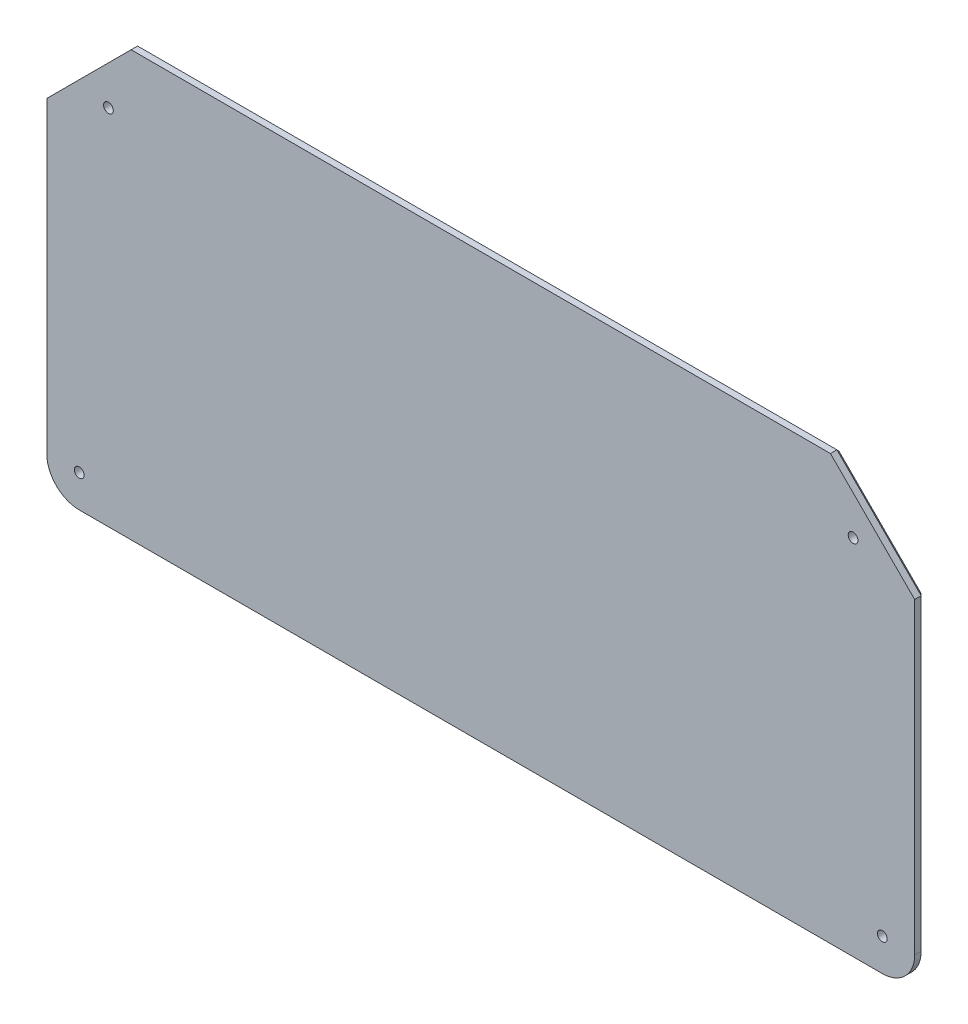
SolidWorks part; units mm, degrees
ref_plane "Front Plane" through (0, 0, 0) normal (0, 0, 1) x (1, 0, 0)
ref_plane "Top Plane" through (0, 0, 0) normal (0, 1, 0) x (1, 0, 0)
ref_plane "Right Plane" through (0, 0, 0) normal (1, 0, 0) x (0, 0, -1)
sketch "Sketch1" plane through (0, 0, 0) normal (0, 0, 1) x (1, 0, 0)
  line L0 (157.8919, 26.2701) -> (191.7747, 29.0915)
  line L1 (157.8919, 26.2701) -> (191.7747, 26.2701)
  line L2 (157.8919, 26.2701) -> (157.8919, 29.0915)
  line L3 (157.8919, 29.0915) -> (191.7747, 29.0915)
  line L4 (191.7747, 26.2701) -> (191.7747, 29.0915)
  line L5 (123.8919, 26.2701) -> (90.0092, 26.2701)
  line L6 (123.8919, 26.2701) -> (123.8919, 29.0915)
  line L7 (123.8919, 29.0915) -> (90.0092, 29.0915)
  line L8 (90.0092, 26.2701) -> (90.0092, 29.0915)
  line L9 (90.0092, 29.0915) -> (123.8919, 26.2701)
  line L10 (168.0919, 58.3601) -> (194.8735, 70.7292)
  line L11 (168.0919, 58.3601) -> (194.8735, 58.3601)
  line L12 (168.0919, 58.3601) -> (168.0919, 70.7292)
  line L13 (168.0919, 70.7292) -> (194.8735, 70.7292)
  line L14 (194.8735, 58.3601) -> (194.8735, 70.7292)
  line L15 (194.8735, 70.7292) -> (224.3587, 70.7292)
  line L16 (194.8735, 70.7292) -> (194.8735, 69.7923)
  line L17 (194.8735, 69.7923) -> (224.3587, 69.7923)
  line L18 (224.3587, 70.7292) -> (224.3587, 69.7923)
  line L19 (224.3587, 69.7923) -> (253.5106, 69.7923)
  line L20 (224.3587, 69.7923) -> (224.3587, 65.2742)
  line L21 (224.3587, 65.2742) -> (253.5106, 65.2742)
  line L22 (253.5106, 69.7923) -> (253.5106, 65.2742)
  line L23 (224.3587, 69.7923) -> (194.8735, 70.7292)
  line L24 (253.5106, 65.2742) -> (224.3587, 69.7923)
  line L25 (170.7502, 87.7401) -> (168.0919, 58.3601)
  line L26 (168.0919, 58.3601) -> (170.7502, 58.3601)
  line L27 (168.0919, 58.3601) -> (168.0919, 87.7401)
  line L28 (168.0919, 87.7401) -> (170.7502, 87.7401)
  line L29 (170.7502, 58.3601) -> (170.7502, 87.7401)
  line L30 (52.9966, 89.4705) -> (24.4119, 82.1791)
  line L31 (24.4119, 82.1791) -> (52.9966, 82.1791)
  line L32 (24.4119, 82.1791) -> (24.4119, 89.4705)
  line L33 (24.4119, 89.4705) -> (52.9966, 89.4705)
  line L34 (52.9966, 82.1791) -> (52.9966, 89.4705)
  line L35 (82.4966, 89.4705) -> (109.0019, 89.4705)
  line L36 (82.4966, 89.4705) -> (82.4966, 76.5201)
  line L37 (82.4966, 76.5201) -> (109.0019, 76.5201)
  line L38 (109.0019, 89.4705) -> (109.0019, 76.5201)
  line L39 (92.4554, 117.2387) -> (82.4966, 117.2387)
  line L40 (92.4554, 117.2387) -> (92.4554, 89.4705)
  line L41 (92.4554, 89.4705) -> (82.4966, 89.4705)
  line L42 (82.4966, 117.2387) -> (82.4966, 89.4705)
  line L43 (92.4554, 117.2387) -> (82.4966, 89.4705)
  line L44 (109.0019, 76.5201) -> (82.4966, 89.4705)
  circle A0 centre (123.8919, 26.2701) radius 14.25
  circle A1 centre (157.8919, 26.2701) radius 14.25
  circle A2 centre (90.0092, 29.0915) radius 14.25
  circle A3 centre (191.7747, 29.0915) radius 14.25
  circle A4 centre (82.4966, 89.4705) radius 11.25
  circle A5 centre (92.4554, 117.2387) radius 11.25
  circle A6 centre (52.9966, 89.4705) radius 11.25
  circle A7 centre (109.0019, 76.5201) radius 11.25
  circle A8 centre (24.4119, 82.1791) radius 11.25
  circle A9 centre (170.7502, 87.7401) radius 11.25
  circle A10 centre (168.0919, 58.3601) radius 11.25
  circle A11 centre (197.5318, 100.1092) radius 11.25
  circle A12 centre (194.8735, 70.7292) radius 11.25
  circle A13 centre (227.0169, 99.1723) radius 11.25
  circle A14 centre (224.3587, 69.7923) radius 11.25
  circle A15 centre (256.1689, 94.6541) radius 11.25
  circle A16 centre (253.5106, 65.2742) radius 11.25
  circle A17 centre (24.4119, 82.1791) radius 12
  circle A18 centre (52.9966, 89.4705) radius 12
  circle A19 centre (92.4554, 117.2387) radius 12
  circle A20 centre (82.4966, 89.4705) radius 12
  circle A21 centre (109.0019, 76.5201) radius 12
  circle A22 centre (168.0919, 58.3601) radius 12
  circle A23 centre (194.8735, 70.7292) radius 12
  circle A24 centre (224.3587, 69.7923) radius 12
  circle A25 centre (253.5106, 65.2742) radius 12
  circle A26 centre (256.1689, 94.6541) radius 12
  circle A27 centre (227.0169, 99.1723) radius 12
  circle A28 centre (197.5318, 100.1092) radius 12
  circle A29 centre (170.7502, 87.7401) radius 12
  circle A30 centre (191.7747, 29.0915) radius 15
  circle A31 centre (157.8919, 26.2701) radius 15
  circle A32 centre (123.8919, 26.2701) radius 15
  circle A33 centre (90.0092, 29.0915) radius 15
  circle A34 centre (173.429, 117.1182) radius 11.25
  circle A35 centre (173.429, 117.1182) radius 12
  dimension "D1" = 28.5
  dimension "D2" = 22.5
  dimension "D3" = 0.75
  dimension "D4" = 0.75
  dimension "D34" = 34
  dimension "D5" = 29.5
  dimension "D6" = 29.5
  dimension "D7" = 29.5
  dimension "D8" = 29.5
  dimension "D9" = 29.5
  dimension "D10" = 29.5
  dimension "D11" = 29.5
  dimension "D12" = 29.5
  dimension "D13" = 29.5
  dimension "D14" = 29.5
  dimension "D15" = 29.5
  dimension "D16" = 29.5
  dimension "D17" = 29.5
  dimension "D18" = 29.5
  dimension "D19" = 34
  dimension "D20" = 34
  dimension "D21" = 32.09
  dimension "D22" = 10.2
  dimension "D23" = 4.76
  dimension "D24" = 4.76
  dimension "D25" = 24.79
  dimension "D26" = 1.82
  dimension "D27" = 8.81
  dimension "D28" = 84.83
  dimension "D29" = 75.69
  dimension "D30" = 70.27
  dimension "D31" = 26.04
  dimension "D32" = 14.89
  dimension "D33" = 50.25
  dimension "D35" = 29.5
  dimension "D36" = 29.5
sketch "Sketch4" plane through (-30.2083, 20.075, 0) normal (0, 0, 1) x (0.9781, -0.2079, 0)
  line L0 (86.1706, 94.1917) -> (105.2206, 75.1417)
  line L1 (67.1206, 94.1917) -> (86.1706, 94.1917)
  line L2 (67.1206, 94.1917) -> (67.1206, 75.1417)
  line L3 (67.1206, 75.1417) -> (86.1706, 75.1417)
  line L4 (86.1706, 94.1917) -> (86.1706, 75.1417)
  line L5 (86.1706, 94.1917) -> (105.2206, 94.1917)
  line L6 (86.1706, 94.1917) -> (86.1706, 75.1417)
  line L7 (86.1706, 75.1417) -> (105.2206, 75.1417)
  line L8 (105.2206, 94.1917) -> (105.2206, 75.1417)
  line L9 (105.2206, 94.1917) -> (124.2706, 94.1917)
  line L10 (105.2206, 94.1917) -> (105.2206, 75.1417)
  line L11 (105.2206, 75.1417) -> (124.2706, 75.1417)
  line L12 (124.2706, 94.1917) -> (124.2706, 75.1417)
  line L13 (86.1706, 94.1917) -> (105.2206, 94.1917)
  line L14 (86.1706, 94.1917) -> (86.1706, 113.2417)
  line L15 (86.1706, 113.2417) -> (105.2206, 113.2417)
  line L16 (105.2206, 94.1917) -> (105.2206, 113.2417)
  line L17 (66.9585, 85.1784) -> (124.4326, 84.1551)
  point P14 (95.6956, 84.6667)
  point P15 (95.6956, 84.6667)
  dimension "D1" = 19.05
sketch "Sketch9" plane through (0, 0, 0) normal (0, 0, 1) x (1, 0, 0)
  line L1 (17.3619, 89.2291) -> (31.4619, 89.2291)
  line L2 (17.3619, 89.2291) -> (17.3619, 75.1291)
  line L3 (17.3619, 75.1291) -> (31.4619, 75.1291)
  line L4 (31.4619, 89.2291) -> (31.4619, 75.1291)
  line L5 (45.9466, 96.5205) -> (60.0466, 96.5205)
  line L6 (45.9466, 96.5205) -> (45.9466, 82.4205)
  line L7 (45.9466, 82.4205) -> (60.0466, 82.4205)
  line L8 (60.0466, 96.5205) -> (60.0466, 82.4205)
  line L9 (75.4466, 96.5205) -> (89.5466, 96.5205)
  line L10 (75.4466, 96.5205) -> (75.4466, 82.4205)
  line L11 (75.4466, 82.4205) -> (89.5466, 82.4205)
  line L12 (89.5466, 96.5205) -> (89.5466, 82.4205)
  line L13 (101.9519, 83.5701) -> (116.0519, 83.5701)
  line L14 (101.9519, 83.5701) -> (101.9519, 69.4701)
  line L15 (101.9519, 69.4701) -> (116.0519, 69.4701)
  line L16 (116.0519, 83.5701) -> (116.0519, 69.4701)
  line L17 (85.4054, 124.2887) -> (99.5054, 124.2887)
  line L18 (85.4054, 124.2887) -> (85.4054, 110.1887)
  line L19 (85.4054, 110.1887) -> (99.5054, 110.1887)
  line L20 (99.5054, 124.2887) -> (99.5054, 110.1887)
  line L21 (82.9592, 36.1415) -> (97.0592, 36.1415)
  line L22 (82.9592, 36.1415) -> (82.9592, 22.0415)
  line L23 (82.9592, 22.0415) -> (97.0592, 22.0415)
  line L24 (97.0592, 36.1415) -> (97.0592, 22.0415)
  line L25 (116.8419, 33.3201) -> (130.9419, 33.3201)
  line L26 (116.8419, 33.3201) -> (116.8419, 19.2201)
  line L27 (116.8419, 19.2201) -> (130.9419, 19.2201)
  line L28 (130.9419, 33.3201) -> (130.9419, 19.2201)
  line L29 (150.8419, 33.3201) -> (164.9419, 33.3201)
  line L30 (150.8419, 33.3201) -> (150.8419, 19.2201)
  line L31 (150.8419, 19.2201) -> (164.9419, 19.2201)
  line L32 (164.9419, 33.3201) -> (164.9419, 19.2201)
  line L33 (184.7247, 36.1415) -> (198.8247, 36.1415)
  line L34 (184.7247, 36.1415) -> (184.7247, 22.0415)
  line L35 (184.7247, 22.0415) -> (198.8247, 22.0415)
  line L36 (198.8247, 36.1415) -> (198.8247, 22.0415)
  line L37 (260.5606, 58.2242) -> (246.4606, 58.2242)
  line L38 (260.5606, 58.2242) -> (260.5606, 72.3242)
  line L39 (260.5606, 72.3242) -> (246.4606, 72.3242)
  line L40 (246.4606, 58.2242) -> (246.4606, 72.3242)
  line L41 (217.3087, 76.8423) -> (231.4087, 76.8423)
  line L42 (217.3087, 76.8423) -> (217.3087, 62.7423)
  line L43 (217.3087, 62.7423) -> (231.4087, 62.7423)
  line L44 (231.4087, 76.8423) -> (231.4087, 62.7423)
  line L45 (187.8235, 77.7792) -> (201.9235, 77.7792)
  line L46 (187.8235, 77.7792) -> (187.8235, 63.6792)
  line L47 (187.8235, 63.6792) -> (201.9235, 63.6792)
  line L48 (201.9235, 77.7792) -> (201.9235, 63.6792)
  line L49 (161.0419, 65.4101) -> (175.1419, 65.4101)
  line L50 (161.0419, 65.4101) -> (161.0419, 51.3101)
  line L51 (161.0419, 51.3101) -> (175.1419, 51.3101)
  line L52 (175.1419, 65.4101) -> (175.1419, 51.3101)
  line L53 (163.7002, 94.7901) -> (177.8002, 94.7901)
  line L54 (163.7002, 94.7901) -> (163.7002, 80.6901)
  line L55 (163.7002, 80.6901) -> (177.8002, 80.6901)
  line L56 (177.8002, 94.7901) -> (177.8002, 80.6901)
  line L57 (190.4818, 107.1592) -> (204.5818, 107.1592)
  line L58 (190.4818, 107.1592) -> (190.4818, 93.0592)
  line L59 (190.4818, 93.0592) -> (204.5818, 93.0592)
  line L60 (204.5818, 107.1592) -> (204.5818, 93.0592)
  line L61 (219.9669, 106.2223) -> (234.0669, 106.2223)
  line L62 (219.9669, 106.2223) -> (219.9669, 92.1223)
  line L63 (219.9669, 92.1223) -> (234.0669, 92.1223)
  line L64 (234.0669, 106.2223) -> (234.0669, 92.1223)
  line L65 (249.1189, 101.7041) -> (263.2189, 101.7041)
  line L66 (249.1189, 101.7041) -> (249.1189, 87.6041)
  line L67 (249.1189, 87.6041) -> (263.2189, 87.6041)
  line L68 (263.2189, 101.7041) -> (263.2189, 87.6041)
  line L69 (166.379, 124.1682) -> (180.479, 124.1682)
  line L70 (166.379, 124.1682) -> (166.379, 110.0682)
  line L71 (166.379, 110.0682) -> (180.479, 110.0682)
  line L72 (180.479, 124.1682) -> (180.479, 110.0682)
  point P72 (24.4119, 89.2291)
  point P74 (52.9966, 96.5205)
  point P76 (82.4966, 96.5205)
  point P78 (92.4554, 124.2887)
  point P80 (109.0019, 83.5701)
  point P82 (90.0092, 36.1415)
  point P84 (123.8919, 33.3201)
  point P86 (157.8919, 33.3201)
  point P88 (191.7747, 36.1415)
  point P90 (168.0919, 65.4101)
  point P92 (170.7502, 94.7901)
  point P94 (173.429, 124.1682)
  point P96 (197.5318, 107.1592)
  point P98 (227.0169, 106.2223)
  point P100 (256.1689, 101.7041)
  point P102 (194.8735, 77.7792)
  point P104 (224.3587, 76.8423)
  point P106 (253.5106, 72.3242)
  point P108 (17.3619, 82.1791)
  point P109 (45.9466, 89.4705)
  point P110 (75.4466, 89.4705)
  point P111 (101.9519, 76.5201)
  point P112 (85.4054, 117.2387)
  point P113 (82.9592, 29.0915)
  point P114 (116.8419, 26.2701)
  point P115 (150.8419, 26.2701)
  point P116 (184.7247, 29.0915)
  point P118 (161.0419, 58.3601)
  point P119 (187.8235, 70.7292)
  point P120 (217.3087, 69.7923)
  point P121 (246.4606, 65.2742)
  point P122 (163.7002, 87.7401)
  point P123 (190.4818, 100.1092)
  point P124 (219.9669, 99.1723)
  point P125 (249.1189, 94.6541)
  point P126 (166.379, 117.1182)
  dimension "D1" = 14.1
sketch "Sketch10" plane through (-22.0981, 19.3454, 0) normal (0, 0, 1) x (0.9781, -0.2079, 0)
  line L1 (61.5108, 90.7441) -> (75.6108, 90.7441)
  line L2 (61.5108, 90.7441) -> (61.5108, 76.6441)
  line L3 (61.5108, 76.6441) -> (75.6108, 76.6441)
  line L4 (75.6108, 90.7441) -> (75.6108, 76.6441)
  line L5 (80.5608, 90.7441) -> (94.6608, 90.7441)
  line L6 (80.5608, 90.7441) -> (80.5608, 76.6441)
  line L7 (80.5608, 76.6441) -> (94.6608, 76.6441)
  line L8 (94.6608, 90.7441) -> (94.6608, 76.6441)
  line L9 (99.6108, 90.7441) -> (113.7108, 90.7441)
  line L10 (99.6108, 90.7441) -> (99.6108, 76.6441)
  line L11 (99.6108, 76.6441) -> (113.7108, 76.6441)
  line L12 (113.7108, 90.7441) -> (113.7108, 76.6441)
  line L13 (80.5608, 109.7941) -> (94.6608, 109.7941)
  line L14 (80.5608, 109.7941) -> (80.5608, 95.6941)
  line L15 (80.5608, 95.6941) -> (94.6608, 95.6941)
  line L16 (94.6608, 109.7941) -> (94.6608, 95.6941)
  line L17 (50.5121, 89.6359) -> (53.4436, 75.8441) construction
  line L18 (59.0358, 93.2191) -> (78.0858, 93.2191) construction
  line L19 (78.0858, 112.2691) -> (97.1358, 112.2691) construction
  line L20 (97.1358, 93.2191) -> (116.1858, 93.2191) construction
  line L21 (78.0858, 93.2191) -> (78.0858, 112.2691) construction
  line L23 (59.0358, 93.2191) -> (59.0358, 74.1691) construction
  point P16 (75.6108, 83.6941)
  point P17 (94.6608, 83.6941)
  point P18 (113.7108, 83.6941)
  point P19 (87.6108, 90.7441)
  point P20 (87.6108, 109.7941)
  point P23 (68.5608, 90.7441)
  point P26 (68.5608, 93.2191)
  point P29 (87.6108, 112.2691)
  point P30 (106.6608, 90.7441)
  point P33 (106.6608, 93.2191)
  point P34 (80.5608, 102.7441)
  point P37 (78.0858, 102.7441)
  point P42 (59.0358, 83.6941)
  point P43 (61.5108, 83.6941)
sketch "Sketch14" plane through (0, 0, 0) normal (0, 0, 1) x (1, 0, 0)
  line L0 (165.1144, 80.6901) -> (163.7002, 82.1043)
  line L1 (163.7002, 93.3758) -> (165.1144, 94.7901)
  line L2 (177.8002, 93.3758) -> (176.386, 94.7901)
  line L3 (179.0648, 110.0682) -> (180.479, 111.4824)
  line L4 (166.379, 111.4824) -> (167.7932, 110.0682)
  line L5 (166.379, 122.754) -> (167.7932, 124.1682)
  line L6 (179.0648, 124.1682) -> (180.479, 122.754)
  line L7 (203.1676, 93.0592) -> (204.5818, 94.4734)
  line L8 (17.3619, 89.2291) -> (17.3619, 75.1291) construction
  line L9 (17.3619, 89.2291) -> (31.4619, 89.2291) construction
  line L10 (17.3619, 87.8149) -> (18.7761, 89.2291)
  line L11 (17.3619, 75.1291) -> (31.4619, 75.1291) construction
  line L12 (31.4619, 89.2291) -> (31.4619, 75.1291) construction
  line L13 (45.9466, 96.5205) -> (60.0466, 96.5205) construction
  line L14 (60.0466, 96.5205) -> (60.0466, 82.4205) construction
  line L15 (45.9466, 96.5205) -> (45.9466, 82.4205) construction
  line L16 (45.9466, 82.4205) -> (60.0466, 82.4205) construction
  line L17 (85.4054, 124.2887) -> (85.4054, 110.1887) construction
  line L18 (85.4054, 124.2887) -> (99.5054, 124.2887) construction
  line L19 (99.5054, 124.2887) -> (99.5054, 110.1887) construction
  line L20 (85.4054, 110.1887) -> (99.5054, 110.1887) construction
  line L21 (101.9519, 83.5701) -> (101.9519, 69.4701) construction
  line L22 (101.9519, 83.5701) -> (116.0519, 83.5701) construction
  line L23 (116.0519, 83.5701) -> (116.0519, 69.4701) construction
  line L24 (101.9519, 69.4701) -> (116.0519, 69.4701) construction
  line L25 (91.2712, 73.6044) -> (105.0631, 70.6729) construction
  line L26 (107.9947, 84.4647) -> (105.0631, 70.6729) construction
  line L27 (94.2028, 87.3963) -> (107.9947, 84.4647) construction
  line L28 (94.2028, 87.3963) -> (91.2712, 73.6044) construction
  line L29 (72.6375, 77.5651) -> (86.4294, 74.6336) construction
  line L30 (89.361, 88.4255) -> (86.4294, 74.6336) construction
  line L31 (75.5691, 91.357) -> (89.361, 88.4255) construction
  line L32 (75.5691, 91.357) -> (72.6375, 77.5651) construction
  line L33 (56.9354, 95.3177) -> (54.0038, 81.5259) construction
  line L34 (56.9354, 95.3177) -> (70.7273, 92.3862) construction
  line L35 (70.7273, 92.3862) -> (67.7957, 78.5943) construction
  line L36 (54.0038, 81.5259) -> (67.7957, 78.5943) construction
  line L37 (76.5983, 96.1988) -> (90.3901, 93.2673) construction
  line L38 (93.3217, 107.0592) -> (90.3901, 93.2673) construction
  line L39 (79.5298, 109.9907) -> (76.5983, 96.1988) construction
  line L40 (79.5298, 109.9907) -> (93.3217, 107.0592) construction
  line L41 (82.9592, 36.1415) -> (82.9592, 22.0415) construction
  line L42 (82.9592, 36.1415) -> (97.0592, 36.1415) construction
  line L43 (82.9592, 22.0415) -> (97.0592, 22.0415) construction
  line L44 (97.0592, 36.1415) -> (97.0592, 22.0415) construction
  line L45 (116.8419, 33.3201) -> (116.8419, 19.2201) construction
  line L46 (116.8419, 33.3201) -> (130.9419, 33.3201) construction
  line L47 (116.8419, 19.2201) -> (130.9419, 19.2201) construction
  line L48 (130.9419, 33.3201) -> (130.9419, 19.2201) construction
  line L49 (150.8419, 33.3201) -> (150.8419, 19.2201) construction
  line L50 (150.8419, 33.3201) -> (164.9419, 33.3201) construction
  line L51 (164.9419, 33.3201) -> (164.9419, 19.2201) construction
  line L52 (150.8419, 19.2201) -> (164.9419, 19.2201) construction
  line L53 (184.7247, 36.1415) -> (184.7247, 22.0415) construction
  line L54 (184.7247, 22.0415) -> (198.8247, 22.0415) construction
  line L55 (198.8247, 36.1415) -> (198.8247, 22.0415) construction
  line L56 (184.7247, 36.1415) -> (198.8247, 36.1415) construction
  line L57 (161.0419, 65.4101) -> (175.1419, 65.4101) construction
  line L58 (175.1419, 65.4101) -> (175.1419, 51.3101) construction
  line L59 (161.0419, 51.3101) -> (175.1419, 51.3101) construction
  line L60 (161.0419, 65.4101) -> (161.0419, 51.3101) construction
  line L61 (187.8235, 77.7792) -> (187.8235, 63.6792) construction
  line L62 (187.8235, 77.7792) -> (201.9235, 77.7792) construction
  line L63 (187.8235, 63.6792) -> (201.9235, 63.6792) construction
  line L64 (201.9235, 77.7792) -> (201.9235, 63.6792) construction
  line L65 (217.3087, 76.8423) -> (217.3087, 62.7423) construction
  line L66 (217.3087, 76.8423) -> (231.4087, 76.8423) construction
  line L67 (231.4087, 76.8423) -> (231.4087, 62.7423) construction
  line L68 (217.3087, 62.7423) -> (231.4087, 62.7423) construction
  line L69 (260.5606, 58.2242) -> (246.4606, 58.2242) construction
  line L70 (260.5606, 58.2242) -> (260.5606, 72.3242) construction
  line L71 (246.4606, 58.2242) -> (246.4606, 72.3242) construction
  line L72 (260.5606, 72.3242) -> (246.4606, 72.3242) construction
  line L73 (249.1189, 101.7041) -> (263.2189, 101.7041) construction
  line L74 (263.2189, 101.7041) -> (263.2189, 87.6041) construction
  line L75 (249.1189, 87.6041) -> (263.2189, 87.6041) construction
  line L76 (249.1189, 101.7041) -> (249.1189, 87.6041) construction
  line L77 (219.9669, 106.2223) -> (219.9669, 92.1223) construction
  line L78 (219.9669, 106.2223) -> (234.0669, 106.2223) construction
  line L79 (234.0669, 106.2223) -> (234.0669, 92.1223) construction
  line L80 (219.9669, 92.1223) -> (234.0669, 92.1223) construction
  line L81 (190.4818, 107.1592) -> (204.5818, 107.1592) construction
  line L82 (204.5818, 107.1592) -> (204.5818, 93.0592) construction
  line L83 (190.4818, 93.0592) -> (204.5818, 93.0592) construction
  line L84 (190.4818, 107.1592) -> (190.4818, 93.0592) construction
  line L85 (163.7002, 94.7901) -> (177.8002, 94.7901) construction
  line L86 (177.8002, 94.7901) -> (177.8002, 80.6901) construction
  line L87 (163.7002, 80.6901) -> (177.8002, 80.6901) construction
  line L88 (163.7002, 94.7901) -> (163.7002, 80.6901) construction
  line L89 (180.479, 124.1682) -> (180.479, 110.0682) construction
  line L90 (166.379, 110.0682) -> (180.479, 110.0682) construction
  line L91 (166.379, 124.1682) -> (166.379, 110.0682) construction
  line L92 (166.379, 124.1682) -> (180.479, 124.1682) construction
  line L93 (17.3619, 76.5433) -> (18.7761, 75.1291)
  line L94 (30.0477, 75.1291) -> (31.4619, 76.5433)
  line L95 (31.4619, 87.8149) -> (30.0477, 89.2291)
  line L96 (45.9466, 95.1063) -> (47.3608, 96.5205)
  line L97 (45.9466, 83.8347) -> (47.3608, 82.4205)
  line L98 (54.2979, 82.9092) -> (55.3871, 81.2318)
  line L99 (58.6323, 82.4205) -> (60.0466, 83.8347)
  line L100 (56.6413, 93.9344) -> (58.3187, 95.0237)
  line L101 (58.6323, 96.5205) -> (60.0466, 95.1063)
  line L102 (69.3439, 92.6802) -> (70.4332, 91.0029)
  line L103 (68.0897, 79.9776) -> (66.4124, 78.8883)
  line L104 (75.2751, 89.9737) -> (76.9524, 91.063)
  line L105 (72.9316, 78.9484) -> (74.0208, 77.2711)
  line L106 (85.0461, 74.9276) -> (86.7234, 76.0169)
  line L107 (89.0669, 87.0421) -> (87.9777, 88.7195)
  line L108 (89.0068, 93.5613) -> (90.6842, 94.6506)
  line L109 (76.8923, 97.5822) -> (77.9816, 95.9048)
  line L110 (91.9384, 107.3532) -> (93.0277, 105.6759)
  line L111 (79.2358, 108.6074) -> (80.9131, 109.6967)
  line L112 (85.4054, 111.6029) -> (86.8196, 110.1887)
  line L113 (98.0912, 110.1887) -> (99.5054, 111.6029)
  line L114 (98.0912, 124.2887) -> (99.5054, 122.8745)
  line L115 (85.4054, 122.8745) -> (86.8196, 124.2887)
  line L116 (93.9088, 86.013) -> (95.5861, 87.1023)
  line L117 (91.5653, 74.9877) -> (92.6546, 73.3104)
  line L118 (103.6798, 70.9669) -> (105.3572, 72.0562)
  line L119 (106.6114, 84.7588) -> (107.7006, 83.0814)
  line L120 (101.9519, 82.1559) -> (103.3662, 83.5701)
  line L121 (101.9519, 70.8843) -> (103.3662, 69.4701)
  line L122 (114.6377, 69.4701) -> (116.0519, 70.8843)
  line L123 (116.0519, 82.1559) -> (114.6377, 83.5701)
  line L124 (82.9592, 34.7272) -> (84.3734, 36.1415)
  line L125 (82.9592, 23.4557) -> (84.3734, 22.0415)
  line L126 (95.645, 22.0415) -> (97.0592, 23.4557)
  line L127 (97.0592, 34.7272) -> (95.645, 36.1415)
  line L128 (116.8419, 31.9059) -> (118.2562, 33.3201)
  line L129 (116.8419, 20.6343) -> (118.2562, 19.2201)
  line L130 (129.5277, 19.2201) -> (130.9419, 20.6343)
  line L131 (130.9419, 31.9059) -> (129.5277, 33.3201)
  line L132 (150.8419, 31.9059) -> (152.2562, 33.3201)
  line L133 (150.8419, 20.6343) -> (152.2562, 19.2201)
  line L134 (163.5277, 19.2201) -> (164.9419, 20.6343)
  line L135 (164.9419, 31.9059) -> (163.5277, 33.3201)
  line L136 (184.7247, 34.7272) -> (186.1389, 36.1415)
  line L137 (184.7247, 23.4557) -> (186.1389, 22.0415)
  line L138 (197.4105, 22.0415) -> (198.8247, 23.4557)
  line L139 (198.8247, 34.7272) -> (197.4105, 36.1415)
  line L140 (173.7277, 51.3101) -> (175.1419, 52.7243)
  line L141 (161.0419, 52.7243) -> (162.4562, 51.3101)
  line L142 (161.0419, 63.9959) -> (162.4562, 65.4101)
  line L143 (173.7277, 65.4101) -> (175.1419, 63.9959)
  line L144 (187.8235, 65.0934) -> (189.2378, 63.6792)
  line L145 (200.5093, 63.6792) -> (201.9235, 65.0934)
  line L146 (200.5093, 77.7792) -> (201.9235, 76.365)
  line L147 (187.8235, 76.365) -> (189.2378, 77.7792)
  line L148 (176.386, 80.6901) -> (177.8002, 82.1043)
  line L149 (204.5818, 105.745) -> (203.1676, 107.1592)
  line L150 (191.896, 107.1592) -> (190.4818, 105.745)
  line L151 (190.4818, 94.4734) -> (191.896, 93.0592)
  line L152 (219.9669, 104.8081) -> (221.3812, 106.2223)
  line L153 (232.6527, 106.2223) -> (234.0669, 104.8081)
  line L154 (234.0669, 93.5365) -> (232.6527, 92.1223)
  line L155 (219.9669, 93.5365) -> (221.3812, 92.1223)
  line L156 (229.9944, 76.8423) -> (231.4087, 75.4281)
  line L157 (217.3087, 75.4281) -> (218.7229, 76.8423)
  line L158 (217.3087, 64.1565) -> (218.7229, 62.7423)
  line L159 (229.9944, 62.7423) -> (231.4087, 64.1565)
  line L160 (259.1464, 72.3242) -> (260.5606, 70.9099)
  line L161 (246.4606, 70.9099) -> (247.8748, 72.3242)
  line L162 (259.1464, 58.2242) -> (260.5606, 59.6384)
  line L163 (247.8748, 58.2242) -> (246.4606, 59.6384)
  line L164 (261.8047, 87.6041) -> (263.2189, 89.0183)
  line L165 (249.1189, 89.0183) -> (250.5331, 87.6041)
  line L166 (249.1189, 100.2899) -> (250.5331, 101.7041)
  line L167 (261.8047, 101.7041) -> (263.2189, 100.2899)
  line L168 (75.4466, 96.5205) -> (75.4466, 82.4205) construction
  line L169 (75.4466, 96.5205) -> (89.5466, 96.5205) construction
  line L170 (89.5466, 96.5205) -> (89.5466, 82.4205) construction
  line L171 (75.4466, 82.4205) -> (89.5466, 82.4205) construction
  line L172 (76.8608, 96.5205) -> (75.4466, 95.1063)
  line L173 (88.1323, 96.5205) -> (89.5466, 95.1063)
  line L174 (89.5466, 83.8347) -> (88.1323, 82.4205)
  line L175 (75.4466, 83.8347) -> (76.8608, 82.4205)
  arc A0 (17.3619, 87.8149) -> (18.7761, 89.2291) centre (18.069, 88.522) cw
  arc A1 (18.7761, 75.1291) -> (17.3619, 76.5433) centre (18.069, 75.8362) cw
  arc A2 (31.4619, 76.5433) -> (30.0477, 75.1291) centre (30.7548, 75.8362) cw
  arc A3 (30.0477, 89.2291) -> (31.4619, 87.8149) centre (30.7548, 88.522) cw
  arc A4 (58.6323, 96.5205) -> (60.0466, 95.1063) centre (59.3394, 95.8134) cw
  arc A5 (45.9466, 95.1063) -> (47.3608, 96.5205) centre (46.6537, 95.8134) cw
  arc A6 (47.3608, 82.4205) -> (45.9466, 83.8347) centre (46.6537, 83.1276) cw
  arc A7 (60.0466, 83.8347) -> (58.6323, 82.4205) centre (59.3394, 83.1276) cw
  arc A8 (85.4054, 122.8745) -> (86.8196, 124.2887) centre (86.1125, 123.5816) cw
  arc A9 (98.0912, 124.2887) -> (99.5054, 122.8745) centre (98.7983, 123.5816) cw
  arc A10 (99.5054, 111.6029) -> (98.0912, 110.1887) centre (98.7983, 110.8958) cw
  arc A11 (85.4054, 111.6029) -> (86.8196, 110.1887) centre (86.1125, 110.8958) ccw
  arc A12 (101.9519, 82.1559) -> (103.3662, 83.5701) centre (102.6591, 82.863) cw
  arc A13 (114.6377, 83.5701) -> (116.0519, 82.1559) centre (115.3448, 82.863) cw
  arc A14 (116.0519, 70.8843) -> (114.6377, 69.4701) centre (115.3448, 70.1772) cw
  arc A15 (101.9519, 70.8843) -> (103.3662, 69.4701) centre (102.6591, 70.1772) ccw
  arc A16 (103.6798, 70.9669) -> (105.3572, 72.0562) centre (104.5185, 71.5115) ccw
  arc A17 (106.6114, 84.7588) -> (107.7006, 83.0814) centre (107.156, 83.9201) cw
  arc A18 (93.9088, 86.013) -> (95.5861, 87.1023) centre (94.7474, 86.5576) cw
  arc A19 (91.5653, 74.9877) -> (92.6546, 73.3104) centre (92.1099, 74.1491) ccw
  arc A20 (85.0461, 74.9276) -> (86.7234, 76.0169) centre (85.8848, 75.4722) ccw
  arc A21 (87.9777, 88.7195) -> (89.0669, 87.0421) centre (88.5223, 87.8808) cw
  arc A22 (75.2751, 89.9737) -> (76.9524, 91.063) centre (76.1137, 90.5183) cw
  arc A23 (72.9316, 78.9484) -> (74.0208, 77.2711) centre (73.4762, 78.1098) ccw
  arc A24 (56.6413, 93.9344) -> (58.3187, 95.0237) centre (57.48, 94.4791) cw
  arc A25 (69.3439, 92.6802) -> (70.4332, 91.0029) centre (69.8886, 91.8415) cw
  arc A26 (68.0897, 79.9776) -> (66.4124, 78.8883) centre (67.2511, 79.433) cw
  arc A27 (54.2979, 82.9092) -> (55.3871, 81.2318) centre (54.8425, 82.0705) ccw
  arc A28 (89.0068, 93.5613) -> (90.6842, 94.6506) centre (89.8455, 94.106) ccw
  arc A29 (76.8923, 97.5822) -> (77.9816, 95.9048) centre (77.4369, 96.7435) ccw
  arc A30 (79.2358, 108.6074) -> (80.9131, 109.6967) centre (80.0744, 109.1521) cw
  arc A31 (91.9384, 107.3532) -> (93.0277, 105.6759) centre (92.483, 106.5145) cw
  arc A32 (82.9592, 34.7272) -> (84.3734, 36.1415) centre (83.6663, 35.4344) cw
  arc A33 (82.9592, 23.4557) -> (84.3734, 22.0415) centre (83.6663, 22.7486) ccw
  arc A34 (95.645, 22.0415) -> (97.0592, 23.4557) centre (96.3521, 22.7486) ccw
  arc A35 (95.645, 36.1415) -> (97.0592, 34.7272) centre (96.3521, 35.4344) cw
  arc A36 (116.8419, 31.9059) -> (118.2562, 33.3201) centre (117.5491, 32.613) cw
  arc A37 (116.8419, 20.6343) -> (118.2562, 19.2201) centre (117.5491, 19.9272) ccw
  arc A38 (129.5277, 19.2201) -> (130.9419, 20.6343) centre (130.2348, 19.9272) ccw
  arc A39 (129.5277, 33.3201) -> (130.9419, 31.9059) centre (130.2348, 32.613) cw
  arc A40 (150.8419, 31.9059) -> (152.2562, 33.3201) centre (151.5491, 32.613) cw
  arc A41 (163.5277, 33.3201) -> (164.9419, 31.9059) centre (164.2348, 32.613) cw
  arc A42 (164.9419, 20.6343) -> (163.5277, 19.2201) centre (164.2348, 19.9272) cw
  arc A43 (150.8419, 20.6343) -> (152.2562, 19.2201) centre (151.5491, 19.9272) ccw
  arc A44 (184.7247, 23.4557) -> (186.1389, 22.0415) centre (185.4318, 22.7486) ccw
  arc A45 (197.4105, 22.0415) -> (198.8247, 23.4557) centre (198.1176, 22.7486) ccw
  arc A46 (197.4105, 36.1415) -> (198.8247, 34.7272) centre (198.1176, 35.4344) cw
  arc A47 (184.7247, 34.7272) -> (186.1389, 36.1415) centre (185.4318, 35.4344) cw
  arc A48 (173.7277, 65.4101) -> (175.1419, 63.9959) centre (174.4348, 64.703) cw
  arc A49 (175.1419, 52.7243) -> (173.7277, 51.3101) centre (174.4348, 52.0172) cw
  arc A50 (161.0419, 52.7243) -> (162.4562, 51.3101) centre (161.7491, 52.0172) ccw
  arc A51 (161.0419, 63.9959) -> (162.4562, 65.4101) centre (161.7491, 64.703) cw
  arc A52 (187.8235, 76.365) -> (189.2378, 77.7792) centre (188.5306, 77.0721) cw
  arc A53 (187.8235, 65.0934) -> (189.2378, 63.6792) centre (188.5306, 64.3863) ccw
  arc A54 (200.5093, 63.6792) -> (201.9235, 65.0934) centre (201.2164, 64.3863) ccw
  arc A55 (200.5093, 77.7792) -> (201.9235, 76.365) centre (201.2164, 77.0721) cw
  arc A56 (217.3087, 75.4281) -> (218.7229, 76.8423) centre (218.0158, 76.1352) cw
  arc A57 (229.9944, 76.8423) -> (231.4087, 75.4281) centre (230.7016, 76.1352) cw
  arc A58 (231.4087, 64.1565) -> (229.9944, 62.7423) centre (230.7016, 63.4494) cw
  arc A59 (217.3087, 64.1565) -> (218.7229, 62.7423) centre (218.0158, 63.4494) ccw
  arc A60 (259.1464, 58.2242) -> (260.5606, 59.6384) centre (259.8535, 58.9313) ccw
  arc A61 (246.4606, 59.6384) -> (247.8748, 58.2242) centre (247.1677, 58.9313) ccw
  arc A62 (246.4606, 70.9099) -> (247.8748, 72.3242) centre (247.1677, 71.617) cw
  arc A63 (259.1464, 72.3242) -> (260.5606, 70.9099) centre (259.8535, 71.617) cw
  arc A64 (261.8047, 101.7041) -> (263.2189, 100.2899) centre (262.5118, 100.997) cw
  arc A65 (263.2189, 89.0183) -> (261.8047, 87.6041) centre (262.5118, 88.3112) cw
  arc A66 (250.5331, 87.6041) -> (249.1189, 89.0183) centre (249.826, 88.3112) cw
  arc A67 (249.1189, 100.2899) -> (250.5331, 101.7041) centre (249.826, 100.997) cw
  arc A68 (219.9669, 104.8081) -> (221.3812, 106.2223) centre (220.674, 105.5152) cw
  arc A69 (232.6527, 106.2223) -> (234.0669, 104.8081) centre (233.3598, 105.5152) cw
  arc A70 (234.0669, 93.5365) -> (232.6527, 92.1223) centre (233.3598, 92.8294) cw
  arc A71 (221.3812, 92.1223) -> (219.9669, 93.5365) centre (220.674, 92.8294) cw
  arc A72 (203.1676, 107.1592) -> (204.5818, 105.745) centre (203.8747, 106.4521) cw
  arc A73 (204.5818, 94.4734) -> (203.1676, 93.0592) centre (203.8747, 93.7663) cw
  arc A74 (191.896, 93.0592) -> (190.4818, 94.4734) centre (191.1889, 93.7663) cw
  arc A75 (190.4818, 105.745) -> (191.896, 107.1592) centre (191.1889, 106.4521) cw
  arc A76 (176.386, 94.7901) -> (177.8002, 93.3758) centre (177.0931, 94.0829) cw
  arc A77 (177.8002, 82.1043) -> (176.386, 80.6901) centre (177.0931, 81.3972) cw
  arc A78 (165.1144, 80.6901) -> (163.7002, 82.1043) centre (164.4073, 81.3972) cw
  arc A79 (163.7002, 93.3758) -> (165.1144, 94.7901) centre (164.4073, 94.0829) cw
  arc A80 (180.479, 111.4824) -> (179.0648, 110.0682) centre (179.7719, 110.7753) cw
  arc A81 (167.7932, 110.0682) -> (166.379, 111.4824) centre (167.0861, 110.7753) cw
  arc A82 (179.0648, 124.1682) -> (180.479, 122.754) centre (179.7719, 123.4611) cw
  arc A83 (166.379, 122.754) -> (167.7932, 124.1682) centre (167.0861, 123.4611) cw
  arc A84 (75.4466, 95.1063) -> (76.8608, 96.5205) centre (76.1537, 95.8134) cw
  arc A85 (88.1323, 96.5205) -> (89.5466, 95.1063) centre (88.8394, 95.8134) cw
  arc A86 (89.5466, 83.8347) -> (88.1323, 82.4205) centre (88.8394, 83.1276) cw
  arc A87 (76.8608, 82.4205) -> (75.4466, 83.8347) centre (76.1537, 83.1276) cw
  dimension "D1" = 45
  dimension "D2" = 1
  dimension "D71" = 45
  dimension "D3" = 45
  dimension "D4" = 45
  dimension "D5" = 45
  dimension "D6" = 45
  dimension "D7" = 45
  dimension "D8" = 45
  dimension "D9" = 45
  dimension "D10" = 45
  dimension "D11" = 45
  dimension "D12" = 45
  dimension "D13" = 45
  dimension "D14" = 45
  dimension "D15" = 45
  dimension "D16" = 45
  dimension "D17" = 45
  dimension "D18" = 45
  dimension "D19" = 45
  dimension "D20" = 45
  dimension "D21" = 45
  dimension "D22" = 45
  dimension "D23" = 45
  dimension "D24" = 45
  dimension "D25" = 45
  dimension "D26" = 45
  dimension "D27" = 45
  dimension "D28" = 45
  dimension "D29" = 45
  dimension "D30" = 45
  dimension "D31" = 45
  dimension "D32" = 45
  dimension "D33" = 45
  dimension "D34" = 45
  dimension "D35" = 45
  dimension "D36" = 45
  dimension "D37" = 45
  dimension "D38" = 45
  dimension "D39" = 45
  dimension "D40" = 45
  dimension "D41" = 45
  dimension "D42" = 45
  dimension "D43" = 45
  dimension "D44" = 45
  dimension "D45" = 45
  dimension "D46" = 45
  dimension "D47" = 45
  dimension "D48" = 45
  dimension "D49" = 45
  dimension "D50" = 45
  dimension "D51" = 45
  dimension "D52" = 45
  dimension "D53" = 45
  dimension "D54" = 45
  dimension "D55" = 45
  dimension "D56" = 45
  dimension "D57" = 45
  dimension "D58" = 45
  dimension "D59" = 45
  dimension "D60" = 45
  dimension "D61" = 45
  dimension "D62" = 45
  dimension "D63" = 45
  dimension "D64" = 45
  dimension "D65" = 45
  dimension "D66" = 45
  dimension "D67" = 45
  dimension "D68" = 45
  dimension "D69" = 45
  dimension "D70" = 45
  dimension "D72" = 45
  dimension "D73" = 45
  dimension "D74" = 45
  dimension "D75" = 45
  dimension "D76" = 45
  dimension "D77" = 45
  dimension "D78" = 45
  dimension "D79" = 45
  dimension "D80" = 45
  dimension "D81" = 45
  dimension "D82" = 45
  dimension "D83" = 45
  dimension "D84" = 45
  dimension "D85" = 45
  dimension "D86" = 45
  dimension "D87" = 45
  dimension "D88" = 45
  dimension "D89" = 45
sketch "Sketch16" plane through (0, 0, 0) normal (0, 0, 1) x (1, 0, 0)
  line L0 (81.0092, 30.6915) -> (99.0092, 30.6915)
  line L5 (17.3619, 89.2291) -> (17.3619, 75.1291) construction
  line L6 (81.0092, 30.6915) -> (81.0092, 27.4915)
  line L7 (17.3619, 75.1291) -> (31.4619, 75.1291) construction
  line L8 (15.4119, 83.7791) -> (33.4119, 83.7791)
  line L9 (15.4119, 83.7791) -> (15.4119, 80.5791)
  line L10 (15.4119, 80.5791) -> (33.4119, 80.5791)
  line L11 (33.4119, 83.7791) -> (33.4119, 80.5791)
  line L12 (81.0092, 27.4915) -> (99.0092, 27.4915)
  line L13 (99.0092, 30.6915) -> (99.0092, 27.4915)
  line L14 (114.8919, 27.8701) -> (132.8919, 27.8701)
  line L15 (114.8919, 27.8701) -> (114.8919, 24.6701)
  line L16 (114.8919, 24.6701) -> (132.8919, 24.6701)
  line L17 (132.8919, 27.8701) -> (132.8919, 24.6701)
  line L18 (148.8919, 27.8701) -> (166.8919, 27.8701)
  line L19 (148.8919, 27.8701) -> (148.8919, 24.6701)
  line L20 (148.8919, 24.6701) -> (166.8919, 24.6701)
  line L21 (166.8919, 27.8701) -> (166.8919, 24.6701)
  line L22 (182.7747, 30.6915) -> (200.7747, 30.6915)
  line L23 (182.7747, 30.6915) -> (182.7747, 27.4915)
  line L24 (182.7747, 27.4915) -> (200.7747, 27.4915)
  line L25 (200.7747, 30.6915) -> (200.7747, 27.4915)
  line L26 (43.9966, 91.0705) -> (61.9966, 91.0705)
  line L27 (43.9966, 91.0705) -> (43.9966, 87.8705)
  line L28 (43.9966, 87.8705) -> (61.9966, 87.8705)
  line L29 (61.9966, 91.0705) -> (61.9966, 87.8705)
  line L30 (73.4966, 91.0705) -> (91.4966, 91.0705)
  line L31 (73.4966, 91.0705) -> (73.4966, 87.8705)
  line L32 (73.4966, 87.8705) -> (91.4966, 87.8705)
  line L33 (91.4966, 91.0705) -> (91.4966, 87.8705)
  line L34 (100.0019, 78.1201) -> (118.0019, 78.1201)
  line L35 (100.0019, 78.1201) -> (100.0019, 74.9201)
  line L36 (100.0019, 74.9201) -> (118.0019, 74.9201)
  line L37 (118.0019, 78.1201) -> (118.0019, 74.9201)
  line L38 (83.4554, 118.8387) -> (101.4554, 118.8387)
  line L39 (83.4554, 118.8387) -> (83.4554, 115.6387)
  line L40 (83.4554, 115.6387) -> (101.4554, 115.6387)
  line L41 (101.4554, 118.8387) -> (101.4554, 115.6387)
  line L42 (164.429, 118.7182) -> (182.429, 118.7182)
  line L43 (164.429, 118.7182) -> (164.429, 115.5182)
  line L44 (164.429, 115.5182) -> (182.429, 115.5182)
  line L45 (182.429, 118.7182) -> (182.429, 115.5182)
  line L46 (161.7502, 89.3401) -> (179.7502, 89.3401)
  line L47 (161.7502, 89.3401) -> (161.7502, 86.1401)
  line L48 (161.7502, 86.1401) -> (179.7502, 86.1401)
  line L49 (179.7502, 89.3401) -> (179.7502, 86.1401)
  line L50 (188.5318, 101.7092) -> (206.5318, 101.7092)
  line L51 (188.5318, 101.7092) -> (188.5318, 98.5092)
  line L52 (188.5318, 98.5092) -> (206.5318, 98.5092)
  line L53 (206.5318, 101.7092) -> (206.5318, 98.5092)
  line L54 (159.0919, 59.9601) -> (177.0919, 59.9601)
  line L55 (159.0919, 59.9601) -> (159.0919, 56.7601)
  line L56 (159.0919, 56.7601) -> (177.0919, 56.7601)
  line L57 (177.0919, 59.9601) -> (177.0919, 56.7601)
  line L58 (185.8735, 72.3292) -> (203.8735, 72.3292)
  line L59 (185.8735, 72.3292) -> (185.8735, 69.1292)
  line L60 (185.8735, 69.1292) -> (203.8735, 69.1292)
  line L61 (203.8735, 72.3292) -> (203.8735, 69.1292)
  line L62 (218.0169, 100.7723) -> (236.0169, 100.7723)
  line L63 (218.0169, 100.7723) -> (218.0169, 97.5723)
  line L64 (218.0169, 97.5723) -> (236.0169, 97.5723)
  line L65 (236.0169, 100.7723) -> (236.0169, 97.5723)
  line L66 (215.3587, 71.3923) -> (233.3587, 71.3923)
  line L67 (215.3587, 71.3923) -> (215.3587, 68.1923)
  line L68 (215.3587, 68.1923) -> (233.3587, 68.1923)
  line L69 (233.3587, 71.3923) -> (233.3587, 68.1923)
  line L70 (247.1689, 96.2541) -> (265.1689, 96.2541)
  line L71 (247.1689, 96.2541) -> (247.1689, 93.0541)
  line L72 (247.1689, 93.0541) -> (265.1689, 93.0541)
  line L73 (265.1689, 96.2541) -> (265.1689, 93.0541)
  line L74 (244.5106, 66.8742) -> (262.5106, 66.8742)
  line L75 (244.5106, 66.8742) -> (244.5106, 63.6742)
  line L76 (244.5106, 63.6742) -> (262.5106, 63.6742)
  line L77 (262.5106, 66.8742) -> (262.5106, 63.6742)
  circle A0 centre (15.4119, 82.1791) radius 1.6
  circle A1 centre (33.4119, 82.1791) radius 1.6
  circle A2 centre (81.0092, 29.0915) radius 1.6
  circle A3 centre (99.0092, 29.0915) radius 1.6
  circle A4 centre (114.8919, 26.2701) radius 1.6
  circle A5 centre (132.8919, 26.2701) radius 1.6
  circle A6 centre (148.8919, 26.2701) radius 1.6
  circle A7 centre (166.8919, 26.2701) radius 1.6
  circle A8 centre (182.7747, 29.0915) radius 1.6
  circle A9 centre (200.7747, 29.0915) radius 1.6
  circle A10 centre (43.9966, 89.4705) radius 1.6
  circle A11 centre (61.9966, 89.4705) radius 1.6
  circle A12 centre (73.4966, 89.4705) radius 1.6
  circle A13 centre (91.4966, 89.4705) radius 1.6
  circle A14 centre (100.0019, 76.5201) radius 1.6
  circle A15 centre (118.0019, 76.5201) radius 1.6
  circle A16 centre (83.4554, 117.2387) radius 1.6
  circle A17 centre (101.4554, 117.2387) radius 1.6
  circle A18 centre (164.429, 117.1182) radius 1.6
  circle A19 centre (182.429, 117.1182) radius 1.6
  circle A20 centre (161.7502, 87.7401) radius 1.6
  circle A21 centre (179.7502, 87.7401) radius 1.6
  circle A22 centre (188.5318, 100.1092) radius 1.6
  circle A23 centre (206.5318, 100.1092) radius 1.6
  circle A24 centre (159.0919, 58.3601) radius 1.6
  circle A25 centre (177.0919, 58.3601) radius 1.6
  circle A26 centre (185.8735, 70.7292) radius 1.6
  circle A27 centre (203.8735, 70.7292) radius 1.6
  circle A28 centre (218.0169, 99.1723) radius 1.6
  circle A29 centre (236.0169, 99.1723) radius 1.6
  circle A30 centre (215.3587, 69.7923) radius 1.6
  circle A31 centre (233.3587, 69.7923) radius 1.6
  circle A32 centre (247.1689, 94.6541) radius 1.6
  circle A33 centre (265.1689, 94.6541) radius 1.6
  circle A34 centre (244.5106, 65.2742) radius 1.6
  circle A35 centre (262.5106, 65.2742) radius 1.6
  point P2 (24.4119, 75.1291)
  point P6 (17.3619, 82.1791)
  point P14 (24.4119, 80.5791)
  point P53 (90.0092, 30.6915)
  point P57 (123.8919, 27.8701)
  point P60 (157.8919, 27.8701)
  point P63 (191.7747, 30.6915)
  point P73 (52.9966, 91.0705)
  point P83 (82.4966, 91.0705)
  point P93 (109.0019, 78.1201)
  point P103 (92.4554, 118.8387)
  point P113 (173.429, 118.7182)
  point P123 (170.7502, 89.3401)
  point P133 (197.5318, 101.7092)
  point P143 (168.0919, 59.9601)
  point P153 (194.8735, 72.3292)
  point P163 (227.0169, 100.7723)
  point P173 (224.3587, 71.3923)
  point P183 (256.1689, 96.2541)
  point P193 (253.5106, 66.8742)
  dimension "D1" = 3.2
  dimension "D2" = 18
sketch "Sketch8" plane through (0, 0, 0) normal (0, 0, 1) x (1, 0, 0)
  line L0 (52.2844, 74.6389) -> (82.4966, 89.4705)
  line L1 (86.9403, 110.9459) -> (79.0189, 73.6784)
  line L2 (77.6235, 112.9262) -> (96.2572, 108.9655) construction
  line L3 (69.702, 75.6588) -> (88.3357, 71.6981) construction
  line L4 (53.3861, 72.3947) -> (55.5425, 73.4534)
  line L5 (99.6829, 63.2465) -> (101.1557, 61.3487)
  line L6 (103.1308, 62.8814) -> (82.4966, 89.4705)
  line L13 (93.9017, 130.158) -> (94.0202, 130.4883)
  line L14 (99.5495, 128.1325) -> (99.6679, 128.4628)
  line L16 (99.4417, 62.7418) -> (100.7607, 61.0421)
  line L17 (55.5377, 72.894) -> (53.6064, 71.9459)
  line L19 (82.4966, 89.4705) -> (96.8441, 129.4755)
  circle A1 centre (57.4203, 106.4022) radius 2.5
  circle A2 centre (106.0456, 106.2134) radius 2.5
  circle A3 centre (76.7673, 63.0854) radius 2.5
  circle A4 centre (52.9966, 89.4705) radius 13
  circle A6 centre (92.4554, 117.2387) radius 13
  circle A7 centre (109.0019, 76.5201) radius 13
  circle A8 centre (82.4966, 89.4705) radius 25
  arc A10 (50.3337, 102.1949) -> (81.377, 124.0408) centre (40.5107, 149.1329) ccw
  circle A11 centre (103.1308, 62.8814) radius 2.5
  circle A12 centre (52.2844, 74.6389) radius 2.5
  circle A13 centre (96.8441, 129.4755) radius 2.5
  circle A14 centre (52.2844, 74.6389) radius 3
  circle A15 centre (103.1308, 62.8814) radius 3
  circle A16 centre (96.8441, 129.4755) radius 3
  arc A17 (104.9258, 113.5659) -> (115.3756, 87.8504) centre (126.3001, 107.2707) ccw
  arc A18 (45.7038, 78.7088) -> (110.8301, 63.6492) centre (97.7768, 155.5511) ccw
  circle A19 centre (92.4554, 117.2387) radius 15
  circle A20 centre (109.0019, 76.5201) radius 15
  circle A21 centre (52.9966, 89.4705) radius 15
  circle A22 centre (82.4966, 89.4705) radius 27
  arc A23 (44.5818, 77.0531) -> (111.1113, 61.6691) centre (97.7768, 155.5511) ccw
  arc A24 (49.924, 104.1525) -> (79.6727, 125.0873) centre (40.5107, 149.1329) ccw
  arc A25 (106.8443, 113.0008) -> (116.3562, 89.5935) centre (126.3001, 107.2707) ccw
  circle A26 centre (52.9966, 89.4705) radius 12.5
  circle A27 centre (109.0019, 76.5201) radius 12.5
  circle A28 centre (92.4554, 117.2387) radius 12.5
  circle A29 centre (82.4966, 89.4705) radius 24.5
  arc A30 (104.4462, 113.7071) -> (115.1305, 87.4146) centre (126.3001, 107.2707) ccw
  arc A31 (110.7597, 64.1443) -> (45.9842, 79.1227) centre (97.7768, 155.5511) cw
  arc A32 (50.4361, 101.7055) -> (81.8031, 123.7792) centre (40.5107, 149.1329) ccw
  circle A33 centre (52.9966, 89.4705) radius 15.5
  circle A34 centre (109.0019, 76.5201) radius 15.5
  circle A35 centre (92.4554, 117.2387) radius 15.5
  circle A36 centre (82.4966, 89.4705) radius 27.5
  arc A37 (107.3239, 112.8596) -> (116.6013, 90.0293) centre (126.3001, 107.2707) ccw
  arc A38 (111.1816, 61.1741) -> (44.3013, 76.6392) centre (97.7768, 155.5511) cw
  arc A39 (49.8216, 104.6419) -> (79.2466, 125.349) centre (40.5107, 149.1329) ccw
  circle A40 centre (106.0456, 106.2134) radius 3
  circle A41 centre (76.7673, 63.0854) radius 3
  circle A42 centre (57.4203, 106.4022) radius 3
  dimension "D3" = 26
  dimension "D4" = 5
  dimension "D7" = 6
  dimension "D8" = 50
  dimension "D1" = 2
  dimension "D2" = 2
  dimension "D5" = 0.5
  dimension "D6" = 0.5
  dimension "D9" = 0.5
  dimension "D10" = 0.5
sketch "Sketch2" plane through (0, 0, 0) normal (0, 0, 1) x (1, 0, 0)
  line L0 (30.4119, 134.2387) -> (8.4119, 112.2387)
  line L1 (16.4119, 134.2387) -> (264.1689, 134.2387)
  line L2 (8.4119, 126.2387) -> (8.4119, 15.2864)
  line L3 (16.4119, 7.2864) -> (264.1689, 7.2864)
  line L4 (272.1689, 126.2387) -> (272.1689, 15.2864)
  line L5 (16.4119, 136.2387) -> (264.1689, 136.2387)
  line L6 (6.4119, 126.2387) -> (6.4119, 15.2864)
  line L7 (16.4119, 5.2864) -> (264.1689, 5.2864)
  line L8 (274.1689, 126.2387) -> (274.1689, 15.2864)
  line L9 (250.1689, 134.2387) -> (272.1689, 112.2387)
  line L10 (6.4119, 110.2387) -> (32.4119, 136.2387)
  line L11 (248.1689, 136.2387) -> (274.1689, 110.2387)
  line L12 (6.4119, 107.4103) -> (35.2403, 136.2387)
  line L13 (245.3405, 136.2387) -> (274.1689, 107.4103)
  circle A0 centre (24.4119, 82.1791) radius 12 construction
  circle A2 centre (256.1689, 94.6541) radius 12 construction
  arc A3 (264.1689, 136.2387) -> (274.1689, 126.2387) centre (264.1689, 126.2387) cw
  circle A4 centre (123.8919, 26.2701) radius 15 construction
  arc A5 (264.1689, 5.2864) -> (274.1689, 15.2864) centre (264.1689, 15.2864) ccw
  arc A6 (6.4119, 15.2864) -> (16.4119, 5.2864) centre (16.4119, 15.2864) ccw
  arc A7 (16.4119, 136.2387) -> (6.4119, 126.2387) centre (16.4119, 126.2387) ccw
  arc A8 (264.1689, 134.2387) -> (272.1689, 126.2387) centre (264.1689, 126.2387) cw
  arc A9 (264.1689, 7.2864) -> (272.1689, 15.2864) centre (264.1689, 15.2864) ccw
  arc A10 (8.4119, 15.2864) -> (16.4119, 7.2864) centre (16.4119, 15.2864) ccw
  arc A11 (16.4119, 134.2387) -> (8.4119, 126.2387) centre (16.4119, 126.2387) ccw
  circle A12 centre (92.4554, 117.2387) radius 13 construction
  point P4 (12.4119, 82.1791)
  point P5 (92.4554, 130.2387)
  point P8 (268.1689, 94.6541)
  point P14 (124.5912, 11.2864)
  point P36 (30.4119, 134.2387)
  point P39 (250.1689, 134.2387)
  dimension "D9" = 10
  dimension "D10" = 8
  dimension "D1" = 4
  dimension "D2" = 4
  dimension "D3" = 4
  dimension "D4" = 4
  dimension "D5" = 2
  dimension "D6" = 2
  dimension "D7" = 2
  dimension "D8" = 2
  dimension "D11" = 14
  dimension "D12" = 45
  dimension "D13" = 14
  dimension "D14" = 45
  dimension "D15" = 2
  dimension "D16" = 2
sketch "Sketch6" plane through (0, 0, 0) normal (0, 0, 1) x (1, 0, 0)
  line L0 (44.9119, 130.2387) -> (56.9119, 130.2387)
  line L1 (31.4119, 130.2387) -> (43.4119, 130.2387)
  line L2 (31.4119, 130.2387) -> (31.4119, 118.2387)
  line L3 (31.4119, 118.2387) -> (43.4119, 118.2387)
  line L4 (43.4119, 130.2387) -> (43.4119, 118.2387)
  line L5 (34.1619, 133.2387) -> (40.6619, 133.2387)
  line L6 (34.1619, 133.2387) -> (34.1619, 115.2387)
  line L7 (34.1619, 115.2387) -> (40.6619, 115.2387)
  line L8 (40.6619, 133.2387) -> (40.6619, 115.2387)
  line L9 (44.9119, 130.2387) -> (44.9119, 118.2387)
  line L10 (44.9119, 118.2387) -> (56.9119, 118.2387)
  line L11 (56.9119, 130.2387) -> (56.9119, 118.2387)
  line L12 (47.6619, 133.2387) -> (54.1619, 133.2387)
  line L13 (47.6619, 133.2387) -> (47.6619, 115.2387)
  line L14 (47.6619, 115.2387) -> (54.1619, 115.2387)
  line L15 (54.1619, 133.2387) -> (54.1619, 115.2387)
  line L16 (58.4119, 130.2387) -> (70.4119, 130.2387)
  line L17 (58.4119, 130.2387) -> (58.4119, 118.2387)
  line L18 (58.4119, 118.2387) -> (70.4119, 118.2387)
  line L19 (70.4119, 130.2387) -> (70.4119, 118.2387)
  line L20 (61.1619, 133.2387) -> (67.6619, 133.2387)
  line L21 (61.1619, 133.2387) -> (61.1619, 115.2387)
  line L22 (61.1619, 115.2387) -> (67.6619, 115.2387)
  line L23 (67.6619, 133.2387) -> (67.6619, 115.2387)
  line L24 (237.1689, 130.2387) -> (249.1689, 130.2387)
  line L25 (237.1689, 130.2387) -> (237.1689, 118.2387)
  line L26 (237.1689, 118.2387) -> (249.1689, 118.2387)
  line L27 (249.1689, 130.2387) -> (249.1689, 118.2387)
  line L28 (239.9189, 133.2387) -> (246.4189, 133.2387)
  line L29 (239.9189, 133.2387) -> (239.9189, 115.2387)
  line L30 (239.9189, 115.2387) -> (246.4189, 115.2387)
  line L31 (246.4189, 133.2387) -> (246.4189, 115.2387)
  line L32 (223.6689, 130.2387) -> (235.6689, 130.2387)
  line L33 (223.6689, 130.2387) -> (223.6689, 118.2387)
  line L34 (223.6689, 118.2387) -> (235.6689, 118.2387)
  line L35 (235.6689, 130.2387) -> (235.6689, 118.2387)
  line L36 (226.4189, 133.2387) -> (232.9189, 133.2387)
  line L37 (226.4189, 133.2387) -> (226.4189, 115.2387)
  line L38 (226.4189, 115.2387) -> (232.9189, 115.2387)
  line L39 (232.9189, 133.2387) -> (232.9189, 115.2387)
  line L40 (210.1689, 130.2387) -> (222.1689, 130.2387)
  line L41 (210.1689, 130.2387) -> (210.1689, 118.2387)
  line L42 (210.1689, 118.2387) -> (222.1689, 118.2387)
  line L43 (222.1689, 130.2387) -> (222.1689, 118.2387)
  line L44 (212.9189, 133.2387) -> (219.4189, 133.2387)
  line L45 (212.9189, 133.2387) -> (212.9189, 115.2387)
  line L46 (212.9189, 115.2387) -> (219.4189, 115.2387)
  line L47 (219.4189, 133.2387) -> (219.4189, 115.2387)
  line L48 (16.4119, 134.2387) -> (264.1689, 134.2387) construction
  line L49 (8.4119, 126.2387) -> (8.4119, 15.2864) construction
  line L50 (272.1689, 126.2387) -> (272.1689, 15.2864) construction
  circle A0 centre (37.4119, 124.2387) radius 3.4
  circle A1 centre (50.9119, 124.2387) radius 3.4
  circle A2 centre (64.4119, 124.2387) radius 3.4
  circle A3 centre (243.1689, 124.2387) radius 3.4
  circle A4 centre (229.6689, 124.2387) radius 3.4
  circle A5 centre (216.1689, 124.2387) radius 3.4
  point P8 (37.4119, 130.2387)
  point P9 (37.4119, 133.2387)
  point P10 (34.1619, 124.2387)
  point P11 (31.4119, 124.2387)
  point P15 (43.4119, 124.2387)
  point P43 (243.1689, 130.2387)
  point P44 (243.1689, 133.2387)
  point P45 (239.9189, 124.2387)
  point P46 (237.1689, 124.2387)
  point P50 (249.1689, 124.2387)
  dimension "D4" = 6.8
  dimension "D9" = 6.8
  dimension "D1" = 18
  dimension "D2" = 12
  dimension "D3" = 6.5
  dimension "D5" = 3
  dimension "D6" = 18
  dimension "D7" = 12
  dimension "D8" = 6.5
  dimension "D11" = 1
  dimension "D12" = 23
  dimension "D13" = 23
  dimension "D10" = 3
sketch "Sketch13" plane through (0, 0, 0) normal (0, 0, 1) x (1, 0, 0)
  line L1 (115.4554, 133.7387) -> (125.4554, 133.7387)
  line L2 (110.4554, 128.7387) -> (110.4554, 118.7387)
  line L3 (115.4554, 113.7387) -> (125.4554, 113.7387)
  line L4 (130.4554, 128.7387) -> (130.4554, 118.7387)
  line L5 (115.9854, 134.7387) -> (124.9254, 134.7387)
  line L6 (115.9854, 134.7387) -> (115.9854, 127.3887)
  line L7 (115.9854, 127.3887) -> (124.9254, 127.3887)
  line L8 (124.9254, 134.7387) -> (124.9254, 127.3887)
  line L9 (115.5354, 132.9887) -> (116.4354, 132.9887)
  line L10 (115.5354, 132.9887) -> (115.5354, 131.2887)
  line L11 (115.5354, 131.2887) -> (116.4354, 131.2887)
  line L12 (116.4354, 132.9887) -> (116.4354, 131.2887)
  line L13 (114.4554, 120.2387) -> (126.4554, 120.2387)
  line L14 (114.4554, 120.2387) -> (114.4554, 113.7387)
  line L15 (114.4554, 113.7387) -> (126.4554, 113.7387)
  line L16 (126.4554, 120.2387) -> (126.4554, 113.7387)
  line L19 (115.4554, 134.2387) -> (125.4554, 134.2387)
  line L20 (109.9554, 128.7387) -> (109.9554, 118.7387)
  line L21 (115.4554, 113.2387) -> (125.4554, 113.2387)
  line L22 (130.9554, 128.7387) -> (130.9554, 118.7387)
  line L23 (16.4119, 134.2387) -> (264.1689, 134.2387) construction
  arc A0 (125.4554, 134.2387) -> (130.9554, 128.7387) centre (125.4554, 128.7387) cw
  arc A1 (115.4554, 133.7387) -> (110.4554, 128.7387) centre (115.4554, 128.7387) ccw
  arc A2 (125.4554, 133.7387) -> (130.4554, 128.7387) centre (125.4554, 128.7387) cw
  arc A3 (125.4554, 113.7387) -> (130.4554, 118.7387) centre (125.4554, 118.7387) ccw
  arc A4 (110.4554, 118.7387) -> (115.4554, 113.7387) centre (115.4554, 118.7387) ccw
  circle A6 centre (112.9554, 123.7387) radius 2.5
  circle A7 centre (127.9554, 123.7387) radius 2.5
  arc A8 (125.4554, 113.2387) -> (130.9554, 118.7387) centre (125.4554, 118.7387) ccw
  arc A9 (109.9554, 118.7387) -> (115.4554, 113.2387) centre (115.4554, 118.7387) ccw
  arc A10 (115.4554, 134.2387) -> (109.9554, 128.7387) centre (115.4554, 128.7387) ccw
  circle A12 centre (92.4554, 117.2387) radius 15.5 construction
  point P9 (115.9854, 132.1387)
  point P13 (116.4354, 132.1387)
  point P14 (115.9854, 132.9887)
  point P15 (120.4554, 113.7387)
  point P16 (120.4554, 127.3887)
  point P17 (120.4554, 113.7387)
  point P34 (110.4554, 123.7387)
  point P41 (120.4554, 134.2387)
  point P42 (120.4554, 133.7387)
  point P43 (130.9554, 123.7387)
  point P44 (130.4554, 123.7387)
  point P53 (107.9554, 117.2387)
  dimension "D7" = 6.5
  dimension "D10" = 5
  dimension "D11" = 5
  dimension "D17" = 5.5
  dimension "D1" = 8.94
  dimension "D2" = 7.35
  dimension "D3" = 2.6
  dimension "D4" = 1.7
  dimension "D5" = 0.9
  dimension "D6" = 1
  dimension "D8" = 12
  dimension "D9" = 7.15
  dimension "D12" = 20
  dimension "D13" = 20
  dimension "D14" = 2
  dimension "D15" = 0.5
  dimension "D16" = 0.5
sketch "Sketch5" plane through (0, 0, 0) normal (0, 0, 1) x (1, 0, 0)
  line L0 (130.9554, 128.7387) -> (130.9554, 118.7387) construction
  line L1 (136.9554, 138.2387) -> (158.5554, 138.2387)
  line L2 (136.9554, 138.2387) -> (136.9554, 106.9387)
  line L3 (136.9554, 106.9387) -> (158.5554, 106.9387)
  line L4 (158.5554, 138.2387) -> (158.5554, 106.9387)
  line L5 (141.7554, 106.9387) -> (153.7554, 106.9387)
  line L6 (141.7554, 106.9387) -> (141.7554, 93.2387)
  line L7 (141.7554, 93.2387) -> (153.7554, 93.2387)
  line L8 (153.7554, 106.9387) -> (153.7554, 93.2387)
  line L9 (16.4119, 136.2387) -> (264.1689, 136.2387) construction
  line L11 (139.9804, 102.2387) -> (155.5304, 102.2387)
  line L12 (139.9804, 102.2387) -> (139.9804, 91.2387)
  line L13 (139.9804, 91.2387) -> (155.5304, 91.2387)
  line L14 (155.5304, 102.2387) -> (155.5304, 91.2387)
  point P8 (147.7554, 106.9387)
  point P9 (147.7554, 106.9387)
  point P18 (147.7554, 93.2387)
  point P19 (147.7554, 102.2387)
  dimension "D1" = 6
  dimension "D2" = 2
  dimension "D3" = 31.3
  dimension "D4" = 21.6
  dimension "D5" = 12
  dimension "D6" = 13.7
  dimension "D7" = 15.55
  dimension "D8" = 11
  dimension "D9" = 2
sketch "Sketch3" plane through (0, 0, 0) normal (0, 0, 1) x (1, 0, 0)
  line L0 (123.8919, 26.2701) -> (157.8919, 26.2701)
  line L1 (125.5419, 80.2945) -> (156.2419, 80.2945)
  line L2 (125.5419, 80.2945) -> (125.5419, 57.0345)
  line L3 (125.5419, 57.0345) -> (156.2419, 57.0345)
  line L4 (156.2419, 80.2945) -> (156.2419, 57.0345)
  line L5 (133.1419, 59.0345) -> (148.6419, 59.0345)
  line L6 (133.1419, 59.0345) -> (133.1419, 55.0345)
  line L7 (133.1419, 55.0345) -> (148.6419, 55.0345)
  line L8 (148.6419, 59.0345) -> (148.6419, 55.0345)
  line L9 (129.0199, 77.1945) -> (152.7639, 77.1945)
  line L10 (129.0199, 77.1945) -> (129.0199, 64.3305)
  line L11 (129.0199, 64.3305) -> (152.7639, 64.3305)
  line L12 (152.7639, 77.1945) -> (152.7639, 64.3305)
  line L13 (133.1419, 55.0345) -> (130.8952, 55.0345)
  line L14 (130.8919, 61.7345) -> (150.8919, 61.7345)
  line L15 (130.8919, 61.7345) -> (130.8919, 56.2345)
  line L16 (130.8919, 56.2345) -> (150.8919, 56.2345)
  line L17 (150.8919, 61.7345) -> (150.8919, 56.2345)
  line L18 (127.5419, 78.2945) -> (154.2419, 78.2945)
  line L19 (130.8919, 56.2345) -> (150.8919, 56.2345)
  line L23 (127.5419, 78.2945) -> (127.5419, 59.0345)
  line L24 (127.5419, 59.0345) -> (154.2419, 59.0345)
  line L25 (154.2419, 78.2945) -> (154.2419, 59.0345)
  line L26 (130.8952, 59.0345) -> (150.8887, 59.0345)
  line L27 (130.8952, 59.0345) -> (130.8952, 53.0345)
  line L28 (130.8952, 53.0345) -> (150.8887, 53.0345)
  line L29 (150.8887, 59.0345) -> (150.8887, 53.0345)
  line L30 (148.6419, 55.0345) -> (150.8887, 55.0345)
  line L31 (274.1689, 126.2387) -> (274.1689, 15.2864) construction
  point P16 (140.8919, 55.0345)
  point P17 (140.8919, 57.0345)
  point P18 (140.8919, 64.3305)
  point P19 (140.8919, 26.2701)
  point P24 (140.8919, 56.2345)
  point P31 (140.8919, 78.2945)
  point P33 (140.8919, 80.2945)
  point P35 (140.8919, 59.0345)
  point P36 (125.5419, 68.6645)
  point P37 (127.5419, 68.6645)
  point P39 (130.8952, 54.0345)
  point P41 (150.8919, 59.0345)
  point P46 (274.1689, 70.7625)
  point P47 (152.7639, 70.7625)
  dimension "D1" = 30.7
  dimension "D2" = 23.26
  dimension "D3" = 4
  dimension "D4" = 15.5
  dimension "D5" = 12.864
  dimension "D6" = 23.744
  dimension "D7" = 26.7
  dimension "D8" = 20
  dimension "D9" = 5.5
  dimension "D10" = 6
  dimension "D11" = 1
  dimension "D12" = 2.8
  dimension "D13" = 19.26
  dimension "D14" = 1.1
  dimension "D15" = 5
sketch "Sketch15" plane through (0, 0, 0) normal (0, 0, 1) x (1, 0, 0)
  line L0 (25.4223, 117.2283) -> (255.1585, 117.2283)
  line L1 (16.4119, 15.2864) -> (264.1689, 15.2864)
  line L2 (16.4119, 7.2864) -> (264.1689, 7.2864) construction
  line L4 (6.4119, 107.4103) -> (35.2403, 136.2387) construction
  line L5 (20.8261, 121.8245) -> (25.4223, 117.2283)
  circle A0 centre (25.4223, 117.2283) radius 2.5
  circle A1 centre (255.1585, 117.2283) radius 2.5
  circle A2 centre (264.1689, 15.2864) radius 2.5
  circle A3 centre (16.4119, 15.2864) radius 2.5
  point P8 (140.2904, 117.2283)
  point P9 (140.2904, 15.2864)
  point P12 (140.2904, 7.2864)
  dimension "D1" = 5
  dimension "D2" = 6.5
  dimension "D3" = 90
sketch "Sketch18" plane through (0, 0, 0) normal (0, 0, 1) x (1, 0, 0)
  line L0 (125.5419, 63.0854) -> (125.5419, 99.9387)
  line L1 (130.5419, 104.9387) -> (156.429, 104.9387)
  line L2 (161.429, 109.9387) -> (161.429, 128.7387)
  line L3 (166.429, 133.7387) -> (246.3049, 133.7387)
  line L6 (268.1689, 107.7283) -> (268.1689, 58.2742)
  line L7 (263.1689, 53.2742) -> (211.7747, 53.2742)
  line L8 (206.7747, 48.2742) -> (206.7747, 16.2701)
  line L9 (201.7747, 11.2701) -> (80.0092, 11.2701)
  line L10 (75.0092, 16.2701) -> (75.0092, 33.0854)
  line L11 (70.0092, 38.0854) -> (17.4119, 38.0854)
  line L12 (12.4119, 43.0854) -> (12.4119, 107.7283)
  line L15 (34.2758, 133.7387) -> (71.4119, 133.7387)
  line L16 (76.4119, 128.7387) -> (76.4119, 122.5671)
  line L17 (68.5834, 114.7387) -> (61.4119, 114.7387)
  line L18 (36.4119, 89.7387) -> (36.4119, 63.0854)
  line L19 (41.4119, 58.0854) -> (120.5419, 58.0854)
  line L20 (16.4119, 134.2387) -> (264.1689, 134.2387) construction
  line L21 (250.6585, 129.3851) -> (250.6585, 117.7283)
  line L24 (47.6619, 115.2387) -> (54.1619, 115.2387) construction
  line L25 (239.9189, 133.2387) -> (246.4189, 133.2387) construction
  line L26 (255.6585, 112.7283) -> (263.1689, 112.7283)
  line L27 (24.9223, 112.7283) -> (17.4119, 112.7283)
  line L29 (125.5419, 80.2945) -> (125.5419, 57.0345) construction
  line L30 (32.8616, 133.1529) -> (30.5081, 130.7994)
  line L31 (75.8261, 121.1529) -> (69.9977, 115.3245)
  line L32 (6.4119, 107.4103) -> (35.2403, 136.2387) construction
  line L33 (25.4223, 117.2283) -> (255.1585, 117.2283) construction
  line L35 (27.9119, 126.7387) -> (29.9223, 126.7387)
  line L36 (27.9119, 126.7387) -> (27.9119, 121.7387)
  line L37 (27.9119, 121.7387) -> (29.9223, 121.7387)
  line L40 (247.7191, 133.1529) -> (250.0727, 130.7994)
  line L41 (252.6689, 126.7387) -> (250.6585, 126.7387)
  line L42 (252.6689, 126.7387) -> (252.6689, 121.7387)
  line L43 (252.6689, 121.7387) -> (250.6585, 121.7387)
  line L44 (250.6585, 126.7387) -> (250.6585, 121.7387)
  line L45 (245.3405, 136.2387) -> (274.1689, 107.4103) construction
  line L46 (256.1689, 94.6541) -> (253.5106, 65.2742)
  line L47 (123.8919, 26.2701) -> (157.8919, 26.2701) construction
  line L48 (29.9223, 129.3851) -> (29.9223, 126.7387)
  line L49 (29.9223, 121.7387) -> (29.9223, 117.7283)
  line L50 (20.8261, 121.8245) -> (25.4223, 117.2283) construction
  line L51 (136.9554, 106.9387) -> (158.5554, 106.9387) construction
  line L52 (31.4119, 130.2387) -> (31.4119, 118.2387) construction
  line L53 (70.4119, 130.2387) -> (70.4119, 118.2387) construction
  line L54 (210.1689, 130.2387) -> (210.1689, 118.2387) construction
  line L55 (249.1689, 130.2387) -> (249.1689, 118.2387) construction
  circle A0 centre (73.9119, 124.2387) radius 2.5
  circle A1 centre (255.1585, 117.2283) radius 2.5 construction
  circle A2 centre (24.4119, 82.1791) radius 12 construction
  circle A3 centre (90.0092, 29.0915) radius 15 construction
  circle A4 centre (157.8919, 26.2701) radius 15 construction
  circle A5 centre (191.7747, 29.0915) radius 15 construction
  circle A6 centre (253.5106, 65.2742) radius 12 construction
  circle A7 centre (256.1689, 94.6541) radius 12 construction
  circle A8 centre (173.429, 117.1182) radius 12 construction
  circle A9 centre (76.7673, 63.0854) radius 3 construction
  arc A12 (61.4119, 114.7387) -> (36.4119, 89.7387) centre (61.4119, 89.7387) ccw
  arc A15 (268.1689, 58.2742) -> (263.1689, 53.2742) centre (263.1689, 58.2742) cw
  arc A16 (80.0092, 11.2701) -> (75.0092, 16.2701) centre (80.0092, 16.2701) cw
  arc A17 (206.7747, 16.2701) -> (201.7747, 11.2701) centre (201.7747, 16.2701) cw
  arc A18 (211.7747, 53.2742) -> (206.7747, 48.2742) centre (211.7747, 48.2742) ccw
  arc A19 (161.429, 128.7387) -> (166.429, 133.7387) centre (166.429, 128.7387) cw
  arc A20 (156.429, 104.9387) -> (161.429, 109.9387) centre (156.429, 109.9387) ccw
  arc A21 (125.5419, 99.9387) -> (130.5419, 104.9387) centre (130.5419, 99.9387) cw
  arc A22 (125.5419, 63.0854) -> (120.5419, 58.0854) centre (120.5419, 63.0854) cw
  arc A23 (75.0092, 33.0854) -> (70.0092, 38.0854) centre (70.0092, 33.0854) ccw
  arc A24 (36.4119, 63.0854) -> (41.4119, 58.0854) centre (41.4119, 63.0854) ccw
  arc A25 (17.4119, 38.0854) -> (12.4119, 43.0854) centre (17.4119, 43.0854) cw
  circle A33 centre (27.9119, 124.2387) radius 2.5
  arc A34 (29.9223, 117.7283) -> (24.9223, 112.7283) centre (24.9223, 117.7283) cw
  arc A35 (12.4119, 107.7283) -> (17.4119, 112.7283) centre (17.4119, 107.7283) cw
  arc A36 (268.1689, 107.7283) -> (263.1689, 112.7283) centre (263.1689, 107.7283) ccw
  circle A37 centre (25.4223, 117.2283) radius 2.5 construction
  circle A38 centre (17.4119, 43.0854) radius 2.5
  circle A39 centre (140.8919, 16.2701) radius 2.5
  circle A40 centre (130.5419, 99.9387) radius 2.5
  circle A41 centre (252.6689, 124.2387) radius 2.5
  circle A42 centre (206.6689, 124.2387) radius 2.5
  circle A43 centre (263.1689, 79.9641) radius 2.5
  arc A44 (250.6585, 117.7283) -> (255.6585, 112.7283) centre (255.6585, 117.7283) ccw
  arc A45 (32.8616, 133.1529) -> (34.2758, 133.7387) centre (34.2758, 131.7387) cw
  arc A46 (30.5081, 130.7994) -> (29.9223, 129.3851) centre (31.9223, 129.3851) ccw
  arc A47 (250.0727, 130.7994) -> (250.6585, 129.3851) centre (248.6585, 129.3851) cw
  arc A48 (247.7191, 133.1529) -> (246.3049, 133.7387) centre (246.3049, 131.7387) ccw
  circle A49 centre (28.9223, 120.7387) radius 1
  circle A50 centre (28.9223, 127.7387) radius 1
  circle A51 centre (251.6585, 127.7387) radius 1
  circle A52 centre (251.6585, 120.7387) radius 1
  arc A53 (75.8261, 121.1529) -> (76.4119, 122.5671) centre (74.4119, 122.5671) ccw
  arc A54 (69.9977, 115.3245) -> (68.5834, 114.7387) centre (68.5834, 116.7387) cw
  arc A55 (71.4119, 133.7387) -> (76.4119, 128.7387) centre (71.4119, 128.7387) cw
  point P5 (250.6585, 133.7387)
  point P6 (25.4223, 114.7283)
  point P16 (29.9223, 133.7387)
  point P18 (76.4119, 114.7387)
  point P52 (76.7673, 60.0854)
  point P67 (27.9223, 117.2283)
  point P110 (252.6585, 117.2283)
  point P111 (255.1585, 114.7283)
  point P134 (254.8397, 79.9641)
  point P142 (140.8919, 26.2701)
  point P162 (76.4119, 121.7387)
  point P165 (69.4119, 114.7387)
  dimension "D3" = 5
  dimension "D5" = 0.5
  dimension "D10" = 2
  dimension "D11" = 25
  dimension "D12" = 5
  dimension "D13" = 2
  dimension "D6" = 2
  dimension "D9" = 2
  dimension "D17" = 5
  dimension "D19" = 2
  dimension "D20" = 2
  dimension "D21" = 2
  dimension "D1" = 0.5
  dimension "D2" = 0.5
  dimension "D4" = 0.5
  dimension "D7" = 2
  dimension "D8" = 20
  dimension "D15" = 2
  dimension "D16" = 0.5
  dimension "D18" = 5
  dimension "D22" = 3.5
  dimension "D23" = 3.5
  dimension "D24" = 3.5
  dimension "D25" = 3.5
sketch "Sketch19" plane through (0, 0, 0) normal (0, 0, 1) x (1, 0, 0)
  line L0 (11.9119, 107.7283) -> (11.9119, 43.0854)
  line L1 (17.4119, 37.5854) -> (70.0092, 37.5854)
  line L2 (74.5092, 33.0854) -> (74.5092, 16.2701)
  line L3 (80.0092, 10.7701) -> (201.7747, 10.7701)
  line L4 (207.2747, 16.2701) -> (207.2747, 48.2742)
  line L5 (211.7747, 52.7742) -> (263.1689, 52.7742)
  line L6 (268.6689, 58.2742) -> (268.6689, 107.7283)
  line L7 (263.1689, 113.2283) -> (255.6585, 113.2283)
  line L9 (70.0092, 38.0854) -> (17.4119, 38.0854) construction
  line L12 (24.9223, 113.2283) -> (17.4119, 113.2283)
  line L13 (24.9223, 112.7283) -> (17.4119, 112.7283) construction
  line L14 (75.0092, 16.2701) -> (75.0092, 33.0854) construction
  line L15 (16.4119, 134.2387) -> (264.1689, 134.2387) construction
  line L16 (12.4119, 43.0854) -> (12.4119, 107.7283) construction
  line L17 (201.7747, 11.2701) -> (80.0092, 11.2701) construction
  line L18 (206.7747, 48.2742) -> (206.7747, 16.2701) construction
  line L19 (263.1689, 53.2742) -> (211.7747, 53.2742) construction
  line L20 (268.1689, 107.7283) -> (268.1689, 58.2742) construction
  line L21 (255.6585, 112.7283) -> (263.1689, 112.7283) construction
  line L22 (251.1585, 117.7283) -> (251.1585, 121.2387)
  line L23 (245.3405, 136.2387) -> (274.1689, 107.4103) construction
  line L24 (248.0727, 133.5065) -> (250.4262, 131.1529)
  line L25 (246.3049, 134.2387) -> (166.429, 134.2387)
  line L26 (250.6585, 129.3851) -> (250.6585, 117.7283) construction
  line L27 (251.1585, 129.3851) -> (251.1585, 127.2387)
  line L28 (251.1585, 127.2387) -> (252.6689, 127.2387)
  line L29 (251.1585, 121.2387) -> (252.6689, 121.2387)
  line L30 (252.6689, 121.7387) -> (250.6585, 121.7387) construction
  line L31 (252.6689, 126.7387) -> (250.6585, 126.7387) construction
  line L32 (160.929, 128.7387) -> (160.929, 109.9387)
  line L33 (156.429, 105.4387) -> (130.5419, 105.4387)
  line L34 (125.0419, 99.9387) -> (125.0419, 63.0854)
  line L35 (120.5419, 58.5854) -> (41.4119, 58.5854)
  line L36 (36.9119, 63.0854) -> (36.9119, 89.7387)
  line L37 (61.4119, 114.2387) -> (68.5834, 114.2387)
  line L38 (76.9119, 122.5671) -> (76.9119, 128.7387)
  line L39 (71.4119, 134.2387) -> (34.2758, 134.2387)
  line L40 (76.4119, 128.7387) -> (76.4119, 122.5671) construction
  line L41 (68.5834, 114.7387) -> (61.4119, 114.7387) construction
  line L42 (70.3512, 114.9709) -> (76.1796, 120.7994)
  line L43 (32.5081, 133.5065) -> (30.1545, 131.1529)
  line L44 (75.8261, 121.1529) -> (69.9977, 115.3245) construction
  line L45 (36.4119, 89.7387) -> (36.4119, 63.0854) construction
  line L46 (41.4119, 58.0854) -> (120.5419, 58.0854) construction
  line L47 (125.5419, 63.0854) -> (125.5419, 99.9387) construction
  line L48 (130.5419, 104.9387) -> (156.429, 104.9387) construction
  line L49 (161.429, 109.9387) -> (161.429, 128.7387) construction
  line L50 (166.429, 134.2387) -> (71.4119, 134.2387)
  line L52 (6.4119, 107.4103) -> (35.2403, 136.2387) construction
  line L53 (29.4223, 117.7283) -> (29.4223, 121.2387)
  line L54 (29.4223, 129.3851) -> (29.4223, 127.2387)
  line L55 (29.9223, 129.3851) -> (29.9223, 126.7387) construction
  line L56 (27.9119, 126.7387) -> (29.9223, 126.7387) construction
  line L57 (29.4223, 127.2387) -> (27.9119, 127.2387)
  line L58 (29.4223, 121.2387) -> (27.9119, 121.2387)
  line L59 (27.9119, 121.7387) -> (29.9223, 121.7387) construction
  line L60 (252.6689, 126.7387) -> (252.6689, 121.7387) construction
  arc A0 (252.6689, 127.2387) -> (252.6689, 121.2387) centre (252.6689, 124.2387) cw
  arc A2 (251.1585, 129.3851) -> (250.4262, 131.1529) centre (248.6585, 129.3851) ccw
  arc A3 (248.0727, 133.5065) -> (246.3049, 134.2387) centre (246.3049, 131.7387) ccw
  arc A4 (251.1585, 117.7283) -> (255.6585, 113.2283) centre (255.6585, 117.7283) ccw
  arc A7 (247.7191, 133.1529) -> (246.3049, 133.7387) centre (246.3049, 131.7387) ccw construction
  arc A8 (27.9119, 121.2387) -> (27.9119, 127.2387) centre (27.9119, 124.2387) cw
  arc A9 (76.1796, 120.7994) -> (76.9119, 122.5671) centre (74.4119, 122.5671) ccw
  arc A10 (70.3512, 114.9709) -> (68.5834, 114.2387) centre (68.5834, 116.7387) cw
  arc A11 (30.1545, 131.1529) -> (29.4223, 129.3851) centre (31.9223, 129.3851) ccw
  arc A12 (32.5081, 133.5065) -> (34.2758, 134.2387) centre (34.2758, 131.7387) cw
  arc A13 (125.0419, 63.0854) -> (120.5419, 58.5854) centre (120.5419, 63.0854) cw
  arc A14 (160.929, 109.9387) -> (156.429, 105.4387) centre (156.429, 109.9387) cw
  arc A15 (130.5419, 105.4387) -> (125.0419, 99.9387) centre (130.5419, 99.9387) ccw
  arc A16 (166.429, 134.2387) -> (160.929, 128.7387) centre (166.429, 128.7387) ccw
  arc A17 (268.6689, 107.7283) -> (263.1689, 113.2283) centre (263.1689, 107.7283) ccw
  arc A18 (263.1689, 52.7742) -> (268.6689, 58.2742) centre (263.1689, 58.2742) ccw
  arc A19 (207.2747, 48.2742) -> (211.7747, 52.7742) centre (211.7747, 48.2742) cw
  arc A20 (201.7747, 10.7701) -> (207.2747, 16.2701) centre (201.7747, 16.2701) ccw
  arc A21 (74.5092, 16.2701) -> (80.0092, 10.7701) centre (80.0092, 16.2701) ccw
  arc A22 (11.9119, 43.0854) -> (17.4119, 37.5854) centre (17.4119, 43.0854) ccw
  arc A23 (41.4119, 58.5854) -> (36.9119, 63.0854) centre (41.4119, 63.0854) cw
  arc A24 (11.9119, 107.7283) -> (17.4119, 113.2283) centre (17.4119, 107.7283) cw
  arc A25 (29.4223, 117.7283) -> (24.9223, 113.2283) centre (24.9223, 117.7283) cw
  arc A26 (36.9119, 89.7387) -> (61.4119, 114.2387) centre (61.4119, 89.7387) cw
  arc A27 (76.9119, 128.7387) -> (71.4119, 134.2387) centre (71.4119, 128.7387) ccw
  arc A28 (70.0092, 37.5854) -> (74.5092, 33.0854) centre (70.0092, 33.0854) cw
  circle A29 centre (251.9085, 120.4887) radius 0.75
  circle A30 centre (251.9085, 127.9887) radius 0.75
  circle A31 centre (28.6723, 120.4887) radius 0.75
  circle A32 centre (28.6723, 127.9887) radius 0.75
  point P13 (29.4223, 134.2387)
  point P55 (251.1585, 130.4207)
  point P58 (247.3405, 134.2387)
  point P66 (76.9119, 114.2387)
  point P122 (160.929, 134.2387)
  point P145 (76.9119, 134.2387)
  dimension "D10" = 0.5
  dimension "D13" = 1.5
  dimension "D14" = 0.5
  dimension "D24" = 0.5
  dimension "D25" = 2.5
  dimension "D26" = 4.5
  dimension "D27" = 24.5
  dimension "D28" = 5.5
  dimension "D1" = 0.5
  dimension "D2" = 0.5
  dimension "D3" = 0.5
  dimension "D4" = 0.5
  dimension "D5" = 0.5
  dimension "D6" = 0.5
  dimension "D7" = 0.5
  dimension "D8" = 0.5
  dimension "D9" = 0.5
  dimension "D11" = 0.5
  dimension "D12" = 0.5
  dimension "D15" = 0.5
  dimension "D16" = 0.5
  dimension "D17" = 0.5
  dimension "D20" = 0.5
  dimension "D18" = 0.5
  dimension "D19" = 0.5
  dimension "D21" = 0.5
  dimension "D22" = 0.5
  dimension "D23" = 0.5
sketch "Sketch22" plane through (0, 0, 0) normal (0, 0, 1) x (1, 0, 0)
  line L0 (114.4554, 120.2387) -> (126.4554, 120.2387) construction
  line L1 (125.5419, 94.8666) -> (132.0419, 94.8666)
  line L2 (125.5419, 94.8666) -> (125.5419, 82.8666)
  line L3 (125.5419, 82.8666) -> (132.0419, 82.8666)
  line L4 (132.0419, 94.8666) -> (132.0419, 82.8666)
  line L5 (108.5419, 58.0854) -> (120.5419, 58.0854)
  line L6 (108.5419, 58.0854) -> (108.5419, 51.5854)
  line L7 (108.5419, 51.5854) -> (120.5419, 51.5854)
  line L8 (120.5419, 58.0854) -> (120.5419, 51.5854)
  line L9 (126.4554, 120.2387) -> (126.4554, 113.7387) construction
  line L10 (130.5419, 97.4387) -> (130.5419, 80.2945)
  line L11 (125.5419, 80.2945) -> (156.2419, 80.2945) construction
  line L14 (125.5419, 63.0854) -> (125.5419, 99.9387) construction
  circle A0 centre (130.5419, 99.9387) radius 2.5 construction
  point P19 (130.5419, 88.8666)
  point P21 (125.5419, 88.8666)
sketch "Sketch23" plane through (-19.0974, 26.7768, 0) normal (0, 0, 1) x (0.9781, -0.2079, 0)
  line L0 (111.2025, 119.1867) -> (122.9403, 121.6816) construction
  line L1 (91.2233, 65.7762) -> (103.2233, 65.7762)
  line L2 (91.2233, 65.7762) -> (91.2233, 59.2762)
  line L3 (91.2233, 59.2762) -> (103.2233, 59.2762)
  line L4 (103.2233, 65.7762) -> (103.2233, 59.2762)
  line L5 (122.9403, 121.6816) -> (124.2917, 115.3237) construction
  line L6 (95.7458, 66.2762) -> (114.7958, 66.2762) construction
  arc A0 (52.7761, 64.7332) -> (119.2503, 63.5497) centre (87.5465, 150.2598) ccw construction
  dimension "D1" = 0.5
sketch "Sketch20" plane through (0, 0, 0) normal (0, 0, 1) x (1, 0, 0)
  line L0 (173.429, 117.1182) -> (216.1689, 124.2387)
  line L1 (192.5489, 128.5387) -> (197.0489, 128.5387)
  line L2 (192.5489, 128.5387) -> (192.5489, 119.9387)
  line L3 (192.5489, 119.9387) -> (197.0489, 119.9387)
  line L4 (197.0489, 128.5387) -> (197.0489, 119.9387)
  line L9 (193.2989, 126.7387) -> (196.2989, 126.7387)
  line L10 (193.2989, 126.7387) -> (193.2989, 121.7387)
  line L11 (193.2989, 121.7387) -> (196.2989, 121.7387)
  line L12 (196.2989, 126.7387) -> (196.2989, 121.7387)
  line L13 (201.2589, 131.9887) -> (205.9589, 131.9887)
  line L14 (201.2589, 131.9887) -> (201.2589, 129.7387)
  line L15 (201.2589, 129.7387) -> (205.9589, 129.7387)
  line L16 (205.9589, 131.9887) -> (205.9589, 129.7387)
  line L17 (202.6089, 133.2387) -> (204.6089, 133.2387)
  line L18 (202.6089, 133.2387) -> (202.6089, 131.9887)
  line L19 (202.6089, 131.9887) -> (204.6089, 131.9887)
  line L20 (204.6089, 133.2387) -> (204.6089, 131.9887)
  line L21 (197.0489, 128.5387) -> (210.1689, 128.5387)
  line L22 (210.1689, 130.2387) -> (210.1689, 118.2387) construction
  line L24 (16.4119, 134.2387) -> (264.1689, 134.2387) construction
  point P10 (197.0489, 124.2387)
  point P16 (196.2989, 124.2387)
  point P17 (194.7989, 126.7387)
  point P18 (194.7989, 128.5387)
  point P27 (203.6089, 131.9887)
  point P28 (203.6089, 131.9887)
  point P29 (194.7989, 120.6784)
  point P30 (194.7989, 121.7387)
  point P31 (203.6089, 128.5387)
  point P39 (203.6089, 129.7387)
  dimension "D1" = 8.6
  dimension "D2" = 4.5
  dimension "D3" = 1
  dimension "D5" = 3
  dimension "D6" = 5
  dimension "D7" = 4.7
  dimension "D8" = 2.25
  dimension "D9" = 2
  dimension "D10" = 3.5
sketch "Sketch21" plane through (0, 0, 0) normal (0, 0, 1) x (1, 0, 0)
  line L0 (31.4119, 130.2387) -> (43.4119, 130.2387) construction
  line L1 (31.4119, 131.2387) -> (70.4119, 131.2387)
  line L2 (30.4119, 130.2387) -> (30.4119, 118.2387)
  line L3 (31.4119, 117.2387) -> (70.4119, 117.2387)
  line L4 (71.4119, 130.2387) -> (71.4119, 118.2387)
  line L5 (210.1689, 131.2387) -> (249.1689, 131.2387)
  line L6 (209.1689, 130.2387) -> (209.1689, 118.2387)
  line L7 (210.1689, 117.2387) -> (249.1689, 117.2387)
  line L8 (250.1689, 130.2387) -> (250.1689, 118.2387)
  line L9 (70.4119, 130.2387) -> (70.4119, 118.2387) construction
  line L10 (201.2589, 129.7387) -> (205.9589, 129.7387) construction
  line L11 (192.5489, 129.5387) -> (197.0489, 129.5387)
  line L12 (191.5489, 128.5387) -> (191.5489, 119.9387)
  line L13 (192.5489, 118.9387) -> (197.0489, 118.9387)
  line L14 (198.0489, 128.5387) -> (198.0489, 119.9387)
  line L15 (201.2589, 134.2387) -> (205.9589, 134.2387)
  line L16 (200.2589, 133.2387) -> (200.2589, 129.2387)
  line L17 (201.2589, 128.2387) -> (205.9589, 128.2387)
  line L18 (206.9589, 133.2387) -> (206.9589, 129.2387)
  line L19 (192.5489, 119.9387) -> (197.0489, 119.9387) construction
  line L20 (196.2989, 126.7387) -> (196.2989, 121.7387) construction
  line L21 (192.5489, 128.5387) -> (192.5489, 119.9387) construction
  line L22 (192.5489, 128.5387) -> (197.0489, 128.5387) construction
  line L23 (201.2589, 131.9887) -> (201.2589, 129.7387) construction
  line L25 (202.6089, 133.2387) -> (204.6089, 133.2387) construction
  line L26 (41.4119, 58.0854) -> (41.4119, 38.0854)
  line L27 (42.4119, 55.5854) -> (77.9119, 55.5854)
  line L28 (41.4119, 54.5854) -> (41.4119, 41.5854)
  line L29 (42.4119, 40.5854) -> (77.9119, 40.5854)
  line L30 (78.9119, 54.5854) -> (78.9119, 41.5854)
  line L31 (70.0092, 38.0854) -> (17.4119, 38.0854) construction
  line L32 (132.0419, 94.8666) -> (132.0419, 82.8666) construction
  line L33 (108.5419, 59.0854) -> (120.5419, 59.0854)
  line L34 (107.5419, 58.0854) -> (107.5419, 51.5854)
  line L35 (108.5419, 50.5854) -> (120.5419, 50.5854)
  line L36 (121.5419, 58.0854) -> (121.5419, 51.5854)
  line L37 (125.5419, 95.8666) -> (132.0419, 95.8666)
  line L38 (124.5419, 94.8666) -> (124.5419, 82.8666)
  line L39 (125.5419, 81.8666) -> (132.0419, 81.8666)
  line L40 (133.0419, 94.8666) -> (133.0419, 82.8666)
  line L41 (125.5419, 94.8666) -> (132.0419, 94.8666) construction
  line L42 (108.5419, 58.0854) -> (108.5419, 51.5854) construction
  line L43 (108.5419, 51.5854) -> (120.5419, 51.5854) construction
  line L44 (141.7554, 93.2387) -> (153.7554, 93.2387) construction
  line L45 (137.9804, 104.9387) -> (157.5304, 104.9387)
  line L46 (137.9804, 104.9387) -> (137.9804, 90.2387)
  line L47 (138.9804, 89.2387) -> (156.5304, 89.2387)
  line L48 (157.5304, 104.9387) -> (157.5304, 90.2387)
  line L49 (135.9554, 138.2387) -> (159.5554, 138.2387)
  line L50 (135.9554, 138.2387) -> (135.9554, 105.9387)
  line L51 (136.9554, 104.9387) -> (158.5554, 104.9387)
  line L52 (159.5554, 138.2387) -> (159.5554, 105.9387)
  line L54 (130.5419, 104.9387) -> (156.429, 104.9387) construction
  line L55 (155.5304, 102.2387) -> (155.5304, 91.2387) construction
  line L56 (139.9804, 91.2387) -> (155.5304, 91.2387) construction
  line L57 (136.9554, 138.2387) -> (158.5554, 138.2387) construction
  line L58 (136.9554, 138.2387) -> (136.9554, 106.9387) construction
  line L59 (82.83, 72.3572) -> (81.4785, 65.9992)
  line L60 (82.2488, 64.8132) -> (93.9866, 62.3182)
  line L61 (95.1726, 63.0885) -> (96.524, 69.4464)
  line L62 (95.7538, 70.6325) -> (84.016, 73.1274)
  line L63 (83.8081, 72.1493) -> (95.5459, 69.6543) construction
  line L64 (83.8081, 72.1493) -> (82.4567, 65.7913) construction
  line L65 (95.5459, 69.6543) -> (94.1945, 63.2964) construction
  line L66 (82.4567, 65.7913) -> (94.1945, 63.2964) construction
  arc A0 (249.1689, 131.2387) -> (250.1689, 130.2387) centre (249.1689, 130.2387) cw
  arc A1 (249.1689, 117.2387) -> (250.1689, 118.2387) centre (249.1689, 118.2387) ccw
  arc A2 (210.1689, 131.2387) -> (209.1689, 130.2387) centre (210.1689, 130.2387) ccw
  arc A3 (209.1689, 118.2387) -> (210.1689, 117.2387) centre (210.1689, 118.2387) ccw
  arc A4 (70.4119, 131.2387) -> (71.4119, 130.2387) centre (70.4119, 130.2387) cw
  arc A5 (70.4119, 117.2387) -> (71.4119, 118.2387) centre (70.4119, 118.2387) ccw
  arc A6 (31.4119, 131.2387) -> (30.4119, 130.2387) centre (31.4119, 130.2387) ccw
  arc A7 (30.4119, 118.2387) -> (31.4119, 117.2387) centre (31.4119, 118.2387) ccw
  arc A8 (197.0489, 118.9387) -> (198.0489, 119.9387) centre (197.0489, 119.9387) ccw
  arc A9 (191.5489, 119.9387) -> (192.5489, 118.9387) centre (192.5489, 119.9387) ccw
  arc A10 (192.5489, 129.5387) -> (191.5489, 128.5387) centre (192.5489, 128.5387) ccw
  arc A11 (197.0489, 129.5387) -> (198.0489, 128.5387) centre (197.0489, 128.5387) cw
  arc A12 (201.2589, 134.2387) -> (200.2589, 133.2387) centre (201.2589, 133.2387) ccw
  arc A13 (205.9589, 134.2387) -> (206.9589, 133.2387) centre (205.9589, 133.2387) cw
  arc A14 (205.9589, 128.2387) -> (206.9589, 129.2387) centre (205.9589, 129.2387) ccw
  arc A15 (200.2589, 129.2387) -> (201.2589, 128.2387) centre (201.2589, 129.2387) ccw
  arc A16 (42.4119, 55.5854) -> (41.4119, 54.5854) centre (42.4119, 54.5854) ccw
  arc A17 (41.4119, 41.5854) -> (42.4119, 40.5854) centre (42.4119, 41.5854) ccw
  arc A18 (77.9119, 40.5854) -> (78.9119, 41.5854) centre (77.9119, 41.5854) ccw
  arc A19 (77.9119, 55.5854) -> (78.9119, 54.5854) centre (77.9119, 54.5854) cw
  arc A20 (108.5419, 59.0854) -> (107.5419, 58.0854) centre (108.5419, 58.0854) ccw
  arc A21 (107.5419, 51.5854) -> (108.5419, 50.5854) centre (108.5419, 51.5854) ccw
  arc A22 (120.5419, 50.5854) -> (121.5419, 51.5854) centre (120.5419, 51.5854) ccw
  arc A23 (120.5419, 59.0854) -> (121.5419, 58.0854) centre (120.5419, 58.0854) cw
  arc A24 (125.5419, 95.8666) -> (124.5419, 94.8666) centre (125.5419, 94.8666) ccw
  arc A25 (124.5419, 82.8666) -> (125.5419, 81.8666) centre (125.5419, 82.8666) ccw
  arc A26 (132.0419, 81.8666) -> (133.0419, 82.8666) centre (132.0419, 82.8666) ccw
  arc A27 (132.0419, 95.8666) -> (133.0419, 94.8666) centre (132.0419, 94.8666) cw
  arc A28 (135.9554, 105.9387) -> (136.9554, 104.9387) centre (136.9554, 105.9387) ccw
  arc A29 (158.5554, 104.9387) -> (159.5554, 105.9387) centre (158.5554, 105.9387) ccw
  arc A30 (156.5304, 89.2387) -> (157.5304, 90.2387) centre (156.5304, 90.2387) ccw
  arc A31 (137.9804, 90.2387) -> (138.9804, 89.2387) centre (138.9804, 90.2387) ccw
  arc A32 (93.9866, 62.3182) -> (95.1726, 63.0885) centre (94.1945, 63.2964) ccw
  arc A33 (96.524, 69.4464) -> (95.7538, 70.6325) centre (95.5459, 69.6543) ccw
  arc A34 (82.83, 72.3572) -> (84.016, 73.1274) centre (83.8081, 72.1493) cw
  arc A35 (81.4785, 65.9992) -> (82.2488, 64.8132) centre (82.4567, 65.7913) ccw
  point P8 (50.9119, 131.2387)
  point P11 (229.6689, 131.2387)
  point P12 (30.4119, 124.2387)
  point P41 (203.6089, 128.2387)
  point P44 (203.6089, 129.7387)
  point P45 (194.7989, 118.9387)
  point P48 (194.7989, 119.9387)
  point P49 (198.0489, 124.2387)
  point P52 (196.2989, 124.2387)
  point P81 (41.4119, 48.0854)
  point P82 (41.4119, 48.0854)
  point P102 (132.0419, 88.8666)
  point P103 (133.0419, 88.8666)
  point P106 (128.7919, 94.8666)
  point P107 (128.7919, 95.8666)
  point P110 (108.5419, 54.8354)
  point P111 (107.5419, 54.8354)
  point P112 (114.5419, 50.5854)
  point P115 (114.5419, 51.5854)
  point P118 (41.4119, 55.5854)
  point P123 (78.9119, 40.5854)
  point P126 (78.9119, 55.5854)
  point P151 (147.7554, 138.2387)
  point P152 (147.7554, 104.9387)
  point P155 (147.7554, 93.2387)
  dimension "D3" = 1
  dimension "D9" = 1
  dimension "D14" = 1
  dimension "D19" = 1
  dimension "D24" = 1
  dimension "D1" = 1
  dimension "D2" = 1
  dimension "D4" = 1
  dimension "D5" = 1
  dimension "D6" = 1
  dimension "D7" = 1
  dimension "D8" = 1.5
  dimension "D10" = 15
  dimension "D11" = 37.5
  dimension "D12" = 1
  dimension "D13" = 1
  dimension "D15" = 2
  dimension "D16" = 2
  dimension "D17" = 1
  dimension "D18" = 23.6
  dimension "D20" = 1
  dimension "D21" = 1
  dimension "D22" = 1
  dimension "D23" = 1
sketch "Sketch24" plane through (0, 0, 0) normal (0, 0, 1) x (1, 0, 0)
  line L0 (6.4119, 126.2387) -> (6.4119, 15.2864) construction
  line L1 (30.4223, 10.2864) -> (80.4223, 10.2864)
  line L2 (30.4223, 10.2864) -> (30.4223, 131.2387)
  line L3 (30.4223, 131.2387) -> (80.4223, 131.2387)
  line L4 (80.4223, 10.2864) -> (80.4223, 131.2387)
  line L5 (11.4119, 29.2968) -> (30.4223, 29.2968)
  line L6 (11.4119, 29.2968) -> (11.4119, 112.2283)
  line L7 (11.4119, 112.2283) -> (30.4223, 112.2283)
  line L8 (30.4223, 29.2968) -> (30.4223, 112.2283)
  line L9 (16.4119, 136.2387) -> (264.1689, 136.2387) construction
  line L10 (250.1585, 29.2968) -> (269.1689, 29.2968)
  line L11 (250.1585, 29.2968) -> (250.1585, 112.2283)
  line L12 (250.1585, 112.2283) -> (269.1689, 112.2283)
  line L13 (269.1689, 29.2968) -> (269.1689, 112.2283)
  line L14 (200.1585, 10.2864) -> (250.1585, 10.2864)
  line L15 (200.1585, 10.2864) -> (200.1585, 131.2387)
  line L16 (200.1585, 131.2387) -> (250.1585, 131.2387)
  line L17 (250.1585, 10.2864) -> (250.1585, 131.2387)
  line L18 (274.1689, 126.2387) -> (274.1689, 15.2864) construction
  point P8 (30.4223, 70.7625)
  point P9 (30.4223, 70.7625)
  point P12 (6.4119, 70.7625)
  point P23 (250.1585, 70.7625)
  point P24 (250.1585, 70.7625)
  point P28 (269.1689, 70.7625)
  point P31 (274.1689, 70.7625)
  dimension "D1" = 5
  dimension "D2" = 50
  dimension "D3" = 5
  dimension "D4" = 5
  dimension "D5" = 5
  dimension "D6" = 5
extrude "Boss-Extrude1" add sketch "Sketch2" against normal blind 3 contours A10 L2 L12 L6 A6 L7 A5 L8 L13 L4 A9 L3 | L6 L12 L2 L10 | L2 L12 L1 L0 | L2 A10 L3 A9 L4 L13 L1 L12 | L1 L12 L5 L10 | L13 L5 L12 L1 | L4 L13 L8 L11 | L1 L13 L4 L9 | L5 L13 L1 L11 region at (20.1332, 122.5174, 0) region at (32.8261, 135.2387, 0) region at (7.4119, 109.8245, 0) region at (140.2904, 135.2356, 0) region at (140.2904, 69.778, 0) region at (8.1246, 62.3483, 0) region at (247.7547, 135.2387, 0) region at (260.4475, 122.5174, 0) region at (273.1689, 109.8245, 0)
hole_wizard "Ø3.0mm Dowel Hole1" positions "Sketch25" profile "Sketch26" hole size "Ø3.0" standard "ANSI Metric" end condition through all
sketch "Sketch25" plane through (0, 0, 0) normal (0, 0, 1) x (1, 0, 0)
  point P0 (16.4119, 15.2864)
  point P3 (25.4223, 117.2283)
  point P6 (255.1585, 117.2283)
  point P9 (264.1689, 15.2864)
sketch "Sketch26" plane through (16.4119, 15.2864, 0) normal (1, 0, 0) x (0, -1, 0)
  line L0 (0, 0) -> (0, 3)
  line L1 (0, 3) -> (1.5, 3)
  line L2 (1.5, 3) -> (1.5, 0)
  line L5 (1.5, 0) -> (0, 0)
  line L11 (0, -6.35) -> (0, 107.95) construction
  dimension "Thru Hole Dia." = 3
  dimension "Thru Hole Depth" = 3
chamfer "Chamfer1" distance 1 angle 45 8 edges at (6.4119, 62.7625, -3) (9.3408, 8.2153, -3) (140.2904, 5.2864, -3) (271.24, 8.2153, -3) (19.4119, 123.2387, -3) (274.1689, 62.7625, -3) (261.1689, 123.2387, -3) (140.2904, 136.2387, -3)
